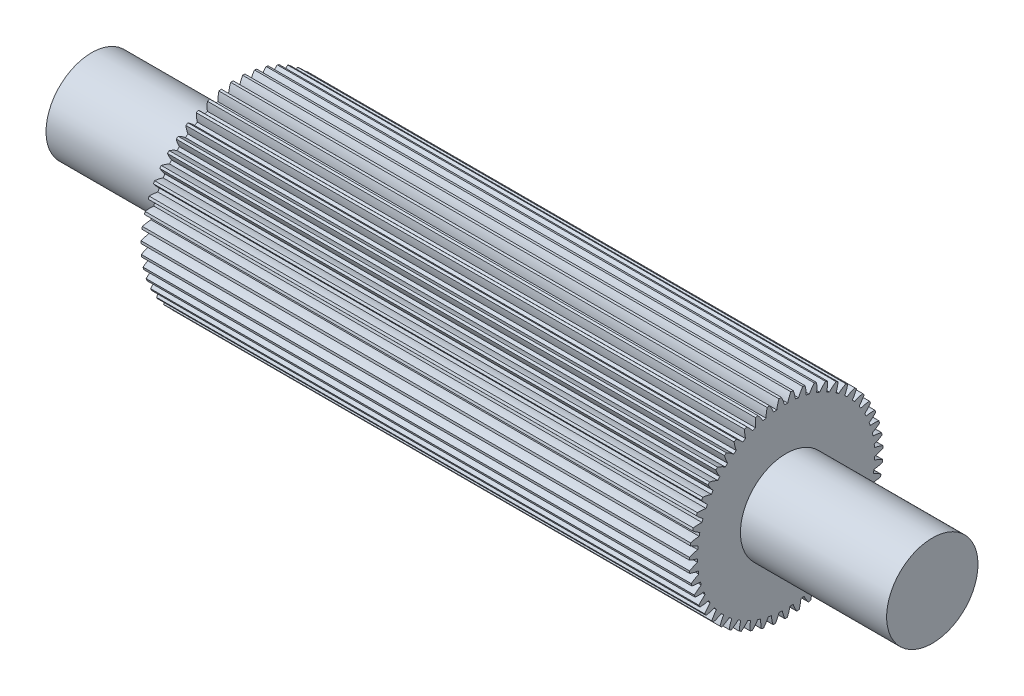
SolidWorks part; units mm, degrees
ref_plane "Plane1" through (0, 0, 0) normal (0, 0, 1) x (1, 0, 0)
ref_plane "Plane2" through (0, 0, 0) normal (0, 1, 0) x (1, 0, 0)
ref_plane "Plane3" through (0, 0, 0) normal (1, 0, 0) x (0, 0, -1)
sketch "HoldingSke" plane through (0, 0, 0) normal (0, 1, 0) x (1, 0, 0)
  line L0 (0, 0) -> (0.3147, -0.3886)
  line L1 (-15, 0) -> (100, 0) construction
  line L2 (0, 0) -> (-2.1039, 2.3779)
  line L3 (0, 0) -> (-11.863, 4.5341)
  line L4 (0, 0) -> (5.4348, 6.7114)
  line L5 (0, 0) -> (-46.8476, -17.4728)
  line L6 (0, 0) -> (-66.317, -44.7443)
  line L7 (-2.1039, 2.3779) -> (15.1161, 80.5027)
  line L8 (-76.2, 54.61) -> (-76.1, 54.61)
  line L9 (-71.009, 38.7566) -> (-53.1078, 45.2721)
  line L10 (-76.2, 71.12) -> (104.1128, 71.12)
  line L11 (0, 0) -> (-80, 0)
  line L12 (-76.2, 101.6) -> (-76.133, 101.6)
  line L13 (24.9733, 27.94) -> (52.9518, 28.4284)
  line L14 (24.9733, 27.94) -> (24.9743, 27.94)
  line L15 (24.9733, 27.94) -> (100.4006, 29.5858)
  line L16 (-63.627, -2) -> (-12.827, -2)
  circle A0 centre (0, 0) radius 0.4
  circle A1 centre (0, 0) radius 37.5
  circle A2 centre (0, 0) radius 37.5
  circle A3 centre (0, 0) radius 0.4
  dimension "Num_teeth" = 51
  dimension "Pitch_radius" = 180.3128
  dimension "Width" = 80
  dimension "Thickness" = 80
sketch "BasProSke" plane through (0, 0, 0) normal (0, 1, 0) x (1, 0, 0)
  line L0 (-10, 0) -> (60, 0) construction
  line L1 (0, 0) -> (0, 53)
  line L2 (0, 0) -> (80, 0)
  line L3 (80, 0) -> (80, 53)
  line L4 (80, 53) -> (0, 53)
  dimension "Thickness" = 80
  dimension "Diameter" = 106
revolve "Base-Revolve" add sketch "BasProSke" angle 360 about L0
sketch "TooCutSke" plane through (0, 0, 0) normal (1, 0, 0) x (0, 0, -1)
  line L1 (0, 0) -> (0, 107) construction
  line L2 (0, 0) -> (-1.6878, 50.9721) construction
  line L3 (0, 0) -> (-6.2767, 101.7652) construction
  line L4 (-1.6878, 50.9721) -> (-3.1383, 50.8826) construction
  arc A0 (0.8589, 48.4914) -> (-0.8589, 48.4914) centre (0, 0) ccw
  arc A1 (2.6252, 52.9604) -> (-2.6252, 52.9604) centre (0, 0) ccw
  circle A2 centre (0, 0) radius 51 construction
  circle A3 centre (0, 0) radius 47.9243 construction
  arc A4 (-0.8589, 48.4914) -> (-2.6252, 52.9604) centre (-20.5819, 43.2796) ccw
  arc A5 (2.6252, 52.9604) -> (0.8589, 48.4914) centre (20.5819, 43.2796) ccw
extrude "ToothCut" cut sketch "TooCutSke" along normal through all
fillet "Breaks" [suppressed] radius 0.04 tangent propagation no
fillet "RootFillets" [suppressed] radius 0.501
pattern_circular "TeethCuts" count 51 every 7.059 about axis through (-10, 0, 0) along (1, 0, 0) of "ToothCut", "RootFillets", "Breaks"
sketch "HubNeaOneSke" plane through (0, 0, 0) normal (-1, 0, 0) x (0, 0, 1)
  circle A0 centre (0, 0) radius 37.5
  dimension "Diameter" = 75
extrude "HubNearOne" [suppressed] add sketch "HubNeaOneSke" along normal blind 20.0001
sketch "HubNeaBotSke" plane through (0, 0, 0) normal (-1, 0, 0) x (0, 0, 1)
  circle A0 centre (0, 0) radius 37.5
  dimension "Diameter" = 75
extrude "HubNearBoth" [suppressed] add sketch "HubNeaBotSke" along normal blind 10
ref_plane "FarPln" through (80, 0, 0) normal (1, 0, 0) x (0, 0, -1)
sketch "HubFarSke" plane through (80, 0, 0) normal (1, 0, 0) x (0, 0, -1)
  circle A0 centre (0, 0) radius 37.5
  dimension "Diameter" = 75
extrude "HubFar" [suppressed] add sketch "HubFarSke" along normal blind 10
sketch "BorSke" plane through (0, 0, 0) normal (1, 0, 0) x (0, 0, -1)
  circle A0 centre (0, 0) radius 0.4
  dimension "Diameter" = 0.8
extrude "Bore" cut sketch "BorSke" along normal mid plane 160.0001
sketch "KeySke" plane through (0, 0, 0) normal (1, 0, 0) x (0, 0, -1)
  line L0 (-0.05, 0) -> (-0.05, 0.5)
  line L1 (-0.05, 0.5) -> (0.05, 0.5)
  line L2 (0.05, 0.5) -> (0.05, 0)
  line L3 (0, 0) -> (0, 34) construction
  line L4 (-0.05, 0) -> (0.05, 0)
extrude "Keyway" [suppressed] cut sketch "KeySke" along normal mid plane 160.0001
pattern_circular "Keyway2" [suppressed] count 2 every 90 about axis through (-10, 0, 0) along (1, 0, 0) reverse direction yes
sketch "草圖2" plane through (80, 0, 0) normal (1, 0, 0) x (0, 0, -1)
  circle A0 centre (0.4, 0) radius 25
  circle A1 centre (0, 0) radius 0.4 construction
  dimension "D1" = 50
extrude "填料-伸長1" add sketch "草圖2" along normal blind 100
extrude "填料-伸長2" add sketch "草圖2<2>" against normal blind 100 from surface starting at face at (0, 0, -0.4)
sketch "草圖2<2>" plane through (80, 0, 0) normal (1, 0, 0) x (0, 0, -1) same geometry as "草圖2"
sketch "草圖3" plane through (0, 0, 0) normal (-1, 0, 0) x (0, 0, 1)
  arc A204 (48.4948, -0.6348) -> (52.9909, 0.9804) centre (43.8929, 19.2393) ccw
  arc A205 (52.9909, 0.9804) -> (52.9508, 2.2836) centre (0, 0) ccw
  arc A206 (52.9508, 2.2836) -> (48.3638, 3.619) centre (44.9941, -16.5007) ccw
  arc A207 (48.3638, 3.619) -> (48.2053, 5.3294) centre (0, 0) ccw
  arc A208 (48.2053, 5.3294) -> (52.4688, 7.485) centre (41.196, 24.4874) ccw
  arc A209 (52.4688, 7.485) -> (52.2688, 8.7733) centre (0, 0) ccw
  arc A210 (52.2688, 8.7733) -> (47.5525, 9.5349) centre (46.6808, -10.8464) ccw
  arc A211 (47.5525, 9.5349) -> (47.185, 11.2129) centre (0, 0) ccw
  arc A212 (47.185, 11.2129) -> (51.1513, 13.876) centre (37.8745, 29.3643) ccw
  arc A213 (51.1513, 13.876) -> (50.7945, 15.13) centre (0, 0) ccw
  arc A214 (50.7945, 15.13) -> (46.0203, 15.3063) centre (47.6599, -5.0277) ccw
  arc A215 (46.0203, 15.3063) -> (45.4494, 16.9264) centre (0, 0) ccw
  arc A216 (45.4494, 16.9264) -> (49.0584, 20.0568) centre (33.9789, 33.7961) ccw
  arc A217 (49.0584, 20.0568) -> (48.5502, 21.2574) centre (0, 0) ccw
  arc A218 (48.5502, 21.2574) -> (43.7905, 20.8457) centre (47.9165, 0.8673) ccw
  arc A219 (43.7905, 20.8457) -> (43.0249, 22.3833) centre (0, 0) ccw
  arc A220 (43.0249, 22.3833) -> (46.2218, 25.9335) centre (29.5682, 37.7155) ccw
  arc A221 (46.2218, 25.9335) -> (45.5699, 27.0625) centre (0, 0) ccw
  arc A222 (45.5699, 27.0625) -> (40.8969, 26.069) centre (47.4467, 6.7491) ccw
  arc A223 (40.8969, 26.069) -> (39.9481, 27.5009) centre (0, 0) ccw
  arc A224 (39.9481, 27.5009) -> (42.6846, 31.417) centre (24.7093, 41.0633) ccw
  arc A225 (42.6846, 31.417) -> (41.8989, 32.4574) centre (0, 0) ccw
  arc A226 (41.8989, 32.4574) -> (37.3834, 30.8972) centre (46.2577, 12.5285) ccw
  arc A227 (37.3834, 30.8972) -> (36.2658, 32.2016) centre (0, 0) ccw
  arc A228 (36.2658, 32.2016) -> (38.5002, 36.4243) centre (19.4758, 43.7885) ccw
  arc A229 (38.5002, 36.4243) -> (37.5927, 37.3603) centre (0, 0) ccw
  arc A230 (37.5927, 37.3603) -> (33.3031, 35.257) centre (44.3675, 18.1181) ccw
  arc A231 (33.3031, 35.257) -> (32.0337, 36.4142) centre (0, 0) ccw
  arc A232 (32.0337, 36.4142) -> (33.7323, 40.8795) centre (13.9471, 45.85) ccw
  arc A233 (33.7323, 40.8795) -> (32.7166, 41.6968) centre (0, 0) ccw
  arc A234 (32.7166, 41.6968) -> (28.7181, 39.0823) centre (41.8047, 23.433) ccw
  arc A235 (28.7181, 39.0823) -> (27.3161, 40.0748) centre (0, 0) ccw
  arc A236 (27.3161, 40.0748) -> (28.453, 44.7149) centre (8.207, 47.2164) ccw
  arc A237 (28.453, 44.7149) -> (27.3446, 45.4013) centre (0, 0) ccw
  arc A238 (27.3446, 45.4013) -> (23.6976, 42.3152) centre (38.6082, 28.3927) ccw
  arc A239 (23.6976, 42.3152) -> (22.1843, 43.1278) centre (0, 0) ccw
  arc A240 (22.1843, 43.1278) -> (22.7424, 47.8726) centre (2.3424, 47.867) ccw
  arc A241 (22.7424, 47.8726) -> (21.558, 48.4175) centre (0, 0) ccw
  arc A242 (21.558, 48.4175) -> (18.318, 44.9066) centre (34.8264, 32.922) ccw
  arc A243 (18.318, 44.9066) -> (16.7163, 45.5271) centre (0, 0) ccw
  arc A244 (16.7163, 45.5271) -> (16.6871, 50.3045) centre (-3.5576, 47.7921) ccw
  arc A245 (16.6871, 50.3045) -> (15.4447, 50.6997) centre (0, 0) ccw
  arc A246 (15.4447, 50.6997) -> (12.6606, 46.8173) centre (30.5167, 36.9523) ccw
  arc A247 (12.6606, 46.8173) -> (10.9948, 47.2363) centre (0, 0) ccw
  arc A248 (10.9948, 47.2363) -> (10.3788, 51.9739) centre (-9.4037, 46.9927) ccw
  arc A249 (10.3788, 51.9739) -> (9.0972, 52.2134) centre (0, 0) ccw
  arc A250 (9.0972, 52.2134) -> (6.8114, 48.0183) centre (25.7444, 40.4223) ccw
  arc A251 (6.8114, 48.0183) -> (5.1067, 48.2294) centre (0, 0) ccw
  arc A252 (5.1067, 48.2294) -> (3.9131, 52.8553) centre (-15.1073, 45.4809) ccw
  arc A253 (3.9131, 52.8553) -> (2.6118, 52.9356) centre (0, 0) ccw
  arc A254 (2.6118, 52.9356) -> (0.8589, 48.4914) centre (20.5819, 43.2796) ccw
  arc A255 (0.8589, 48.4914) -> (-0.8589, 48.4914) centre (0, 0) ccw
  arc A256 (-0.8589, 48.4914) -> (-2.6118, 52.9356) centre (-20.5819, 43.2796) ccw
  arc A257 (-2.6118, 52.9356) -> (-3.9131, 52.8553) centre (0, 0) ccw
  arc A258 (-3.9131, 52.8553) -> (-5.1067, 48.2294) centre (15.1073, 45.4809) ccw
  arc A259 (-5.1067, 48.2294) -> (-6.8114, 48.0183) centre (0, 0) ccw
  arc A260 (-6.8114, 48.0183) -> (-9.0972, 52.2134) centre (-25.7444, 40.4223) ccw
  arc A261 (-9.0972, 52.2134) -> (-10.3788, 51.9739) centre (0, 0) ccw
  arc A262 (-10.3788, 51.9739) -> (-10.9948, 47.2363) centre (9.4037, 46.9927) ccw
  arc A263 (-10.9948, 47.2363) -> (-12.6606, 46.8173) centre (0, 0) ccw
  arc A264 (-12.6606, 46.8173) -> (-15.4447, 50.6997) centre (-30.5167, 36.9523) ccw
  arc A265 (-15.4447, 50.6997) -> (-16.6871, 50.3045) centre (0, 0) ccw
  arc A266 (-16.6871, 50.3045) -> (-16.7163, 45.5271) centre (3.5576, 47.7921) ccw
  arc A267 (-16.7163, 45.5271) -> (-18.318, 44.9066) centre (0, 0) ccw
  arc A268 (-18.318, 44.9066) -> (-21.558, 48.4175) centre (-34.8264, 32.922) ccw
  arc A269 (-21.558, 48.4175) -> (-22.7424, 47.8726) centre (0, 0) ccw
  arc A270 (-22.7424, 47.8726) -> (-22.1843, 43.1278) centre (-2.3424, 47.867) ccw
  arc A271 (-22.1843, 43.1278) -> (-23.6976, 42.3152) centre (0, 0) ccw
  arc A272 (-23.6976, 42.3152) -> (-27.3446, 45.4013) centre (-38.6082, 28.3927) ccw
  arc A273 (-27.3446, 45.4013) -> (-28.453, 44.7149) centre (0, 0) ccw
  arc A274 (-28.453, 44.7149) -> (-27.3161, 40.0748) centre (-8.207, 47.2164) ccw
  arc A275 (-27.3161, 40.0748) -> (-28.7181, 39.0823) centre (0, 0) ccw
  arc A276 (-28.7181, 39.0823) -> (-32.7166, 41.6968) centre (-41.8047, 23.433) ccw
  arc A277 (-32.7166, 41.6968) -> (-33.7323, 40.8795) centre (0, 0) ccw
  arc A278 (-33.7323, 40.8795) -> (-32.0337, 36.4142) centre (-13.9471, 45.85) ccw
  arc A279 (-32.0337, 36.4142) -> (-33.3031, 35.257) centre (0, 0) ccw
  arc A280 (-33.3031, 35.257) -> (-37.5927, 37.3603) centre (-44.3675, 18.1181) ccw
  arc A281 (-37.5927, 37.3603) -> (-38.5002, 36.4243) centre (0, 0) ccw
  arc A282 (-38.5002, 36.4243) -> (-36.2658, 32.2016) centre (-19.4758, 43.7885) ccw
  arc A283 (-36.2658, 32.2016) -> (-37.3834, 30.8972) centre (0, 0) ccw
  arc A284 (-37.3834, 30.8972) -> (-41.8989, 32.4574) centre (-46.2577, 12.5285) ccw
  arc A285 (-41.8989, 32.4574) -> (-42.6846, 31.417) centre (0, 0) ccw
  arc A286 (-42.6846, 31.417) -> (-39.9481, 27.5009) centre (-24.7093, 41.0633) ccw
  arc A287 (-39.9481, 27.5009) -> (-40.8969, 26.069) centre (0, 0) ccw
  arc A288 (-40.8969, 26.069) -> (-45.5699, 27.0625) centre (-47.4467, 6.7491) ccw
  arc A289 (-45.5699, 27.0625) -> (-46.2218, 25.9335) centre (0, 0) ccw
  arc A290 (-46.2218, 25.9335) -> (-43.0249, 22.3833) centre (-29.5682, 37.7155) ccw
  arc A291 (-43.0249, 22.3833) -> (-43.7905, 20.8457) centre (0, 0) ccw
  arc A292 (-43.7905, 20.8457) -> (-48.5502, 21.2574) centre (-47.9165, 0.8673) ccw
  arc A293 (-48.5502, 21.2574) -> (-49.0584, 20.0568) centre (0, 0) ccw
  arc A294 (-49.0584, 20.0568) -> (-45.4494, 16.9264) centre (-33.9789, 33.7961) ccw
  arc A295 (-45.4494, 16.9264) -> (-46.0203, 15.3063) centre (0, 0) ccw
  arc A296 (-46.0203, 15.3063) -> (-50.7945, 15.13) centre (-47.6599, -5.0277) ccw
  arc A297 (-50.7945, 15.13) -> (-51.1513, 13.876) centre (0, 0) ccw
  arc A298 (-51.1513, 13.876) -> (-47.185, 11.2129) centre (-37.8745, 29.3643) ccw
  arc A299 (-47.185, 11.2129) -> (-47.5525, 9.5349) centre (0, 0) ccw
  arc A300 (-47.5525, 9.5349) -> (-52.2688, 8.7733) centre (-46.6808, -10.8464) ccw
  arc A301 (-52.2688, 8.7733) -> (-52.4688, 7.485) centre (0, 0) ccw
  arc A302 (-52.4688, 7.485) -> (-48.2053, 5.3294) centre (-41.196, 24.4874) ccw
  arc A303 (-48.2053, 5.3294) -> (-48.3638, 3.619) centre (0, 0) ccw
  arc A304 (-48.3638, 3.619) -> (-52.9508, 2.2836) centre (-44.9941, -16.5007) ccw
  arc A305 (-52.9508, 2.2836) -> (-52.9909, 0.9804) centre (0, 0) ccw
  arc A306 (-52.9909, 0.9804) -> (-48.4948, -0.6348) centre (-43.8929, 19.2393) ccw
  arc A307 (-48.4948, -0.6348) -> (-48.4419, -2.3517) centre (0, 0) ccw
  arc A308 (-48.4419, -2.3517) -> (-52.8301, -4.2408) centre (-42.6253, -21.9049) ccw
  arc A309 (-52.8301, -4.2408) -> (-52.7098, -5.539) centre (0, 0) ccw
  arc A310 (-52.7098, -5.539) -> (-48.0493, -6.5895) centre (-45.9245, 13.6996) ccw
  arc A311 (-48.0493, -6.5895) -> (-47.7858, -8.2869) centre (0, 0) ccw
  arc A312 (-47.7858, -8.2869) -> (-51.9085, -10.7008) centre (-39.6104, -26.977) ccw
  arc A313 (-51.9085, -10.7008) -> (-51.6296, -11.9744) centre (0, 0) ccw
  arc A314 (-51.6296, -11.9744) -> (-46.8753, -12.4442) centre (-47.26, 7.9521) ccw
  arc A315 (-46.8753, -12.4442) -> (-46.4052, -14.0964) centre (0, 0) ccw
  arc A316 (-46.4052, -14.0964) -> (-50.2001, -16.9986) centre (-35.995, -31.6402) ccw
  arc A317 (-50.2001, -16.9986) -> (-49.7667, -18.2283) centre (0, 0) ccw
  arc A318 (-49.7667, -18.2283) -> (-44.9908, -18.1103) centre (-47.879, 2.0842) ccw
  arc A319 (-44.9908, -18.1103) -> (-44.3212, -19.6922) centre (0, 0) ccw
  arc A320 (-44.3212, -19.6922) -> (-47.7306, -23.0388) centre (-31.8339, -35.8238) ccw
  arc A321 (-47.7306, -23.0388) -> (-47.1495, -24.2059) centre (0, 0) ccw
  arc A322 (-47.1495, -24.2059) -> (-42.4242, -23.5019) centre (-47.7722, -3.8154) ccw
  arc A323 (-42.4242, -23.5019) -> (-41.5654, -24.9895) centre (0, 0) ccw
  arc A324 (-41.5654, -24.9895) -> (-44.5377, -28.7297) centre (-27.1903, -39.4642) ccw
  arc A325 (-44.5377, -28.7297) -> (-43.8175, -29.8165) centre (0, 0) ccw
  arc A326 (-43.8175, -29.8165) -> (-39.2145, -28.5372) centre (-46.9412, -9.6571) ccw
  arc A327 (-39.2145, -28.5372) -> (-38.1794, -29.908) centre (0, 0) ccw
  arc A328 (-38.1794, -29.908) -> (-40.6695, -33.9851) centre (-22.1345, -42.5065) ccw
  arc A329 (-40.6695, -33.9851) -> (-39.8213, -34.9752) centre (0, 0) ccw
  arc A330 (-39.8213, -34.9752) -> (-35.4104, -33.1399) centre (-45.3987, -15.3524) ccw
  arc A331 (-35.4104, -33.1399) -> (-34.2147, -34.3731) centre (0, 0) ccw
  arc A332 (-34.2147, -34.3731) -> (-36.1849, -38.7253) centre (-16.7432, -44.9044) ccw
  arc A333 (-36.1849, -38.7253) -> (-35.2214, -39.6037) centre (0, 0) ccw
  arc A334 (-35.2214, -39.6037) -> (-31.0695, -37.2403) centre (-43.168, -20.8151) ccw
  arc A335 (-31.0695, -37.2403) -> (-29.7313, -38.3171) centre (0, 0) ccw
  arc A336 (-29.7313, -38.3171) -> (-31.1518, -42.8785) centre (-11.0981, -46.6216) ccw
  arc A337 (-31.1518, -42.8785) -> (-30.0876, -43.6318) centre (0, 0) ccw
  arc A338 (-30.0876, -43.6318) -> (-26.2576, -40.7761) centre (-40.2829, -25.9621) ccw
  arc A339 (-26.2576, -40.7761) -> (-24.7972, -41.6803) centre (0, 0) ccw
  arc A340 (-24.7972, -41.6803) -> (-25.6464, -46.3817) centre (-5.2847, -47.6321) ccw
  arc A341 (-25.6464, -46.3817) -> (-24.4977, -46.9985) centre (0, 0) ccw
  arc A342 (-24.4977, -46.9985) -> (-21.0477, -43.6938) centre (-36.7871, -30.7156) ccw
  arc A343 (-21.0477, -43.6938) -> (-19.4872, -44.4117) centre (0, 0) ccw
  arc A344 (-19.4872, -44.4117) -> (-19.7522, -49.1818) centre (0.6087, -47.9205) ccw
  arc A345 (-19.7522, -49.1818) -> (-18.5365, -49.6528) centre (0, 0) ccw
  arc A346 (-18.5365, -49.6528) -> (-15.5187, -45.9491) centre (-32.7337, -35.0035) ccw
  arc A347 (-15.5187, -45.9491) -> (-13.8819, -46.4699) centre (0, 0) ccw
  arc A348 (-13.8819, -46.4699) -> (-13.5586, -51.2363) centre (6.493, -47.4824) ccw
  arc A349 (-13.5586, -51.2363) -> (-12.2943, -51.5544) centre (0, 0) ccw
  arc A350 (-12.2943, -51.5544) -> (-9.7545, -47.5079) centre (-28.184, -38.7608) ccw
  arc A351 (-9.7545, -47.5079) -> (-8.066, -47.8236) centre (0, 0) ccw
  arc A352 (-8.066, -47.8236) -> (-7.1595, -52.5142) centre (12.2788, -46.3246) ccw
  arc A353 (-7.1595, -52.5142) -> (-5.8656, -52.6744) centre (0, 0) ccw
  arc A354 (-5.8656, -52.6744) -> (-3.8424, -48.3466) centre (-23.2072, -41.9305) ccw
  arc A355 (-3.8424, -48.3466) -> (-2.1279, -48.4523) centre (0, 0) ccw
  arc A356 (-2.1279, -48.4523) -> (-0.6519, -52.996) centre (17.8785, -44.4646) ccw
  arc A357 (-0.6519, -52.996) -> (0.6519, -52.996) centre (0, 0) ccw
  arc A358 (0.6519, -52.996) -> (2.1279, -48.4523) centre (-17.8785, -44.4646) ccw
  arc A359 (2.1279, -48.4523) -> (3.8424, -48.3466) centre (0, 0) ccw
  arc A360 (3.8424, -48.3466) -> (5.8656, -52.6744) centre (23.2072, -41.9305) ccw
  arc A361 (5.8656, -52.6744) -> (7.1595, -52.5142) centre (0, 0) ccw
  arc A362 (7.1595, -52.5142) -> (8.066, -47.8236) centre (-12.2788, -46.3246) ccw
  arc A363 (8.066, -47.8236) -> (9.7545, -47.5079) centre (0, 0) ccw
  arc A364 (9.7545, -47.5079) -> (12.2943, -51.5544) centre (28.184, -38.7608) ccw
  arc A365 (12.2943, -51.5544) -> (13.5586, -51.2363) centre (0, 0) ccw
  arc A366 (13.5586, -51.2363) -> (13.8819, -46.4699) centre (-6.493, -47.4824) ccw
  arc A367 (13.8819, -46.4699) -> (15.5187, -45.9491) centre (0, 0) ccw
  arc A368 (15.5187, -45.9491) -> (18.5365, -49.6528) centre (32.7337, -35.0035) ccw
  arc A369 (18.5365, -49.6528) -> (19.7522, -49.1818) centre (0, 0) ccw
  arc A370 (19.7522, -49.1818) -> (19.4872, -44.4117) centre (-0.6087, -47.9205) ccw
  arc A371 (19.4872, -44.4117) -> (21.0477, -43.6938) centre (0, 0) ccw
  arc A372 (21.0477, -43.6938) -> (24.4977, -46.9985) centre (36.7871, -30.7156) ccw
  arc A373 (24.4977, -46.9985) -> (25.6464, -46.3817) centre (0, 0) ccw
  arc A374 (25.6464, -46.3817) -> (24.7972, -41.6803) centre (5.2847, -47.6321) ccw
  arc A375 (24.7972, -41.6803) -> (26.2576, -40.7761) centre (0, 0) ccw
  arc A376 (26.2576, -40.7761) -> (30.0876, -43.6318) centre (40.2829, -25.9621) ccw
  arc A377 (30.0876, -43.6318) -> (31.1518, -42.8785) centre (0, 0) ccw
  arc A378 (31.1518, -42.8785) -> (29.7313, -38.3171) centre (11.0981, -46.6216) ccw
  arc A379 (29.7313, -38.3171) -> (31.0695, -37.2403) centre (0, 0) ccw
  arc A380 (31.0695, -37.2403) -> (35.2214, -39.6037) centre (43.168, -20.8151) ccw
  arc A381 (35.2214, -39.6037) -> (36.1849, -38.7253) centre (0, 0) ccw
  arc A382 (36.1849, -38.7253) -> (34.2147, -34.3731) centre (16.7432, -44.9044) ccw
  arc A383 (34.2147, -34.3731) -> (35.4104, -33.1399) centre (0, 0) ccw
  arc A384 (35.4104, -33.1399) -> (39.8213, -34.9752) centre (45.3987, -15.3524) ccw
  arc A385 (39.8213, -34.9752) -> (40.6695, -33.9851) centre (0, 0) ccw
  arc A386 (40.6695, -33.9851) -> (38.1794, -29.908) centre (22.1345, -42.5065) ccw
  arc A387 (38.1794, -29.908) -> (39.2145, -28.5372) centre (0, 0) ccw
  arc A388 (39.2145, -28.5372) -> (43.8175, -29.8165) centre (46.9412, -9.6571) ccw
  arc A389 (43.8175, -29.8165) -> (44.5377, -28.7297) centre (0, 0) ccw
  arc A390 (44.5377, -28.7297) -> (41.5654, -24.9895) centre (27.1903, -39.4642) ccw
  arc A391 (41.5654, -24.9895) -> (42.4242, -23.5019) centre (0, 0) ccw
  arc A392 (42.4242, -23.5019) -> (47.1495, -24.2059) centre (47.7722, -3.8154) ccw
  arc A393 (47.1495, -24.2059) -> (47.7306, -23.0388) centre (0, 0) ccw
  arc A394 (47.7306, -23.0388) -> (44.3212, -19.6922) centre (31.8339, -35.8238) ccw
  arc A395 (44.3212, -19.6922) -> (44.9908, -18.1103) centre (0, 0) ccw
  arc A396 (44.9908, -18.1103) -> (49.7667, -18.2283) centre (47.879, 2.0842) ccw
  arc A397 (49.7667, -18.2283) -> (50.2001, -16.9986) centre (0, 0) ccw
  arc A398 (50.2001, -16.9986) -> (46.4052, -14.0964) centre (35.995, -31.6402) ccw
  arc A399 (46.4052, -14.0964) -> (46.8753, -12.4442) centre (0, 0) ccw
  arc A400 (46.8753, -12.4442) -> (51.6296, -11.9744) centre (47.26, 7.9521) ccw
  arc A401 (51.6296, -11.9744) -> (51.9085, -10.7008) centre (0, 0) ccw
  arc A402 (51.9085, -10.7008) -> (47.7858, -8.2869) centre (39.6104, -26.977) ccw
  arc A403 (47.7858, -8.2869) -> (48.0493, -6.5895) centre (0, 0) ccw
  arc A404 (48.0493, -6.5895) -> (52.7098, -5.539) centre (45.9245, 13.6996) ccw
  arc A405 (52.7098, -5.539) -> (52.8301, -4.2408) centre (0, 0) ccw
  arc A406 (52.8301, -4.2408) -> (48.4419, -2.3517) centre (42.6253, -21.9049) ccw
  arc A407 (48.4419, -2.3517) -> (48.4948, -0.6348) centre (0, 0) ccw
  arc A408 (48.4948, -0.6348) -> (52.9909, 0.9804) centre (43.8929, 19.2393) ccw
  arc A409 (52.9909, 0.9804) -> (52.9508, 2.2836) centre (0, 0) ccw
  arc A410 (52.9508, 2.2836) -> (48.3638, 3.619) centre (44.9941, -16.5007) ccw
  arc A411 (48.3638, 3.619) -> (48.2053, 5.3294) centre (0, 0) ccw
  arc A412 (48.2053, 5.3294) -> (52.4688, 7.485) centre (41.196, 24.4874) ccw
  arc A413 (52.4688, 7.485) -> (52.2688, 8.7733) centre (0, 0) ccw
  arc A414 (52.2688, 8.7733) -> (47.5525, 9.5349) centre (46.6808, -10.8464) ccw
  arc A415 (47.5525, 9.5349) -> (47.185, 11.2129) centre (0, 0) ccw
  arc A416 (47.185, 11.2129) -> (51.1513, 13.876) centre (37.8745, 29.3643) ccw
  arc A417 (51.1513, 13.876) -> (50.7945, 15.13) centre (0, 0) ccw
  arc A418 (50.7945, 15.13) -> (46.0203, 15.3063) centre (47.6599, -5.0277) ccw
  arc A419 (46.0203, 15.3063) -> (45.4494, 16.9264) centre (0, 0) ccw
  arc A420 (45.4494, 16.9264) -> (49.0584, 20.0568) centre (33.9789, 33.7961) ccw
  arc A421 (49.0584, 20.0568) -> (48.5502, 21.2574) centre (0, 0) ccw
  arc A422 (48.5502, 21.2574) -> (43.7905, 20.8457) centre (47.9165, 0.8673) ccw
  arc A423 (43.7905, 20.8457) -> (43.0249, 22.3833) centre (0, 0) ccw
  arc A424 (43.0249, 22.3833) -> (46.2218, 25.9335) centre (29.5682, 37.7155) ccw
  arc A425 (46.2218, 25.9335) -> (45.5699, 27.0625) centre (0, 0) ccw
  arc A426 (45.5699, 27.0625) -> (40.8969, 26.069) centre (47.4467, 6.7491) ccw
  arc A427 (40.8969, 26.069) -> (39.9481, 27.5009) centre (0, 0) ccw
  arc A428 (39.9481, 27.5009) -> (42.6846, 31.417) centre (24.7093, 41.0633) ccw
  arc A429 (42.6846, 31.417) -> (41.8989, 32.4574) centre (0, 0) ccw
  arc A430 (41.8989, 32.4574) -> (37.3834, 30.8972) centre (46.2577, 12.5285) ccw
  arc A431 (37.3834, 30.8972) -> (36.2658, 32.2016) centre (0, 0) ccw
  arc A432 (36.2658, 32.2016) -> (38.5002, 36.4243) centre (19.4758, 43.7885) ccw
  arc A433 (38.5002, 36.4243) -> (37.5927, 37.3603) centre (0, 0) ccw
  arc A434 (37.5927, 37.3603) -> (33.3031, 35.257) centre (44.3675, 18.1181) ccw
  arc A435 (33.3031, 35.257) -> (32.0337, 36.4142) centre (0, 0) ccw
  arc A436 (32.0337, 36.4142) -> (33.7323, 40.8795) centre (13.9471, 45.85) ccw
  arc A437 (33.7323, 40.8795) -> (32.7166, 41.6968) centre (0, 0) ccw
  arc A438 (32.7166, 41.6968) -> (28.7181, 39.0823) centre (41.8047, 23.433) ccw
  arc A439 (28.7181, 39.0823) -> (27.3161, 40.0748) centre (0, 0) ccw
  arc A440 (27.3161, 40.0748) -> (28.453, 44.7149) centre (8.207, 47.2164) ccw
  arc A441 (28.453, 44.7149) -> (27.3446, 45.4013) centre (0, 0) ccw
  arc A442 (27.3446, 45.4013) -> (23.6976, 42.3152) centre (38.6082, 28.3927) ccw
  arc A443 (23.6976, 42.3152) -> (22.1843, 43.1278) centre (0, 0) ccw
  arc A444 (22.1843, 43.1278) -> (22.7424, 47.8726) centre (2.3424, 47.867) ccw
  arc A445 (22.7424, 47.8726) -> (21.558, 48.4175) centre (0, 0) ccw
  arc A446 (21.558, 48.4175) -> (18.318, 44.9066) centre (34.8264, 32.922) ccw
  arc A447 (18.318, 44.9066) -> (16.7163, 45.5271) centre (0, 0) ccw
  arc A448 (16.7163, 45.5271) -> (16.6871, 50.3045) centre (-3.5576, 47.7921) ccw
  arc A449 (16.6871, 50.3045) -> (15.4447, 50.6997) centre (0, 0) ccw
  arc A450 (15.4447, 50.6997) -> (12.6606, 46.8173) centre (30.5167, 36.9523) ccw
  arc A451 (12.6606, 46.8173) -> (10.9948, 47.2363) centre (0, 0) ccw
  arc A452 (10.9948, 47.2363) -> (10.3788, 51.9739) centre (-9.4037, 46.9927) ccw
  arc A453 (10.3788, 51.9739) -> (9.0972, 52.2134) centre (0, 0) ccw
  arc A454 (9.0972, 52.2134) -> (6.8114, 48.0183) centre (25.7444, 40.4223) ccw
  arc A455 (6.8114, 48.0183) -> (5.1067, 48.2294) centre (0, 0) ccw
  arc A456 (5.1067, 48.2294) -> (3.9131, 52.8553) centre (-15.1073, 45.4809) ccw
  arc A457 (3.9131, 52.8553) -> (2.6118, 52.9356) centre (0, 0) ccw
  arc A458 (2.6118, 52.9356) -> (0.8589, 48.4914) centre (20.5819, 43.2796) ccw
  arc A459 (0.8589, 48.4914) -> (-0.8589, 48.4914) centre (0, 0) ccw
  arc A460 (-0.8589, 48.4914) -> (-2.6118, 52.9356) centre (-20.5819, 43.2796) ccw
  arc A461 (-2.6118, 52.9356) -> (-3.9131, 52.8553) centre (0, 0) ccw
  arc A462 (-3.9131, 52.8553) -> (-5.1067, 48.2294) centre (15.1073, 45.4809) ccw
  arc A463 (-5.1067, 48.2294) -> (-6.8114, 48.0183) centre (0, 0) ccw
  arc A464 (-6.8114, 48.0183) -> (-9.0972, 52.2134) centre (-25.7444, 40.4223) ccw
  arc A465 (-9.0972, 52.2134) -> (-10.3788, 51.9739) centre (0, 0) ccw
  arc A466 (-10.3788, 51.9739) -> (-10.9948, 47.2363) centre (9.4037, 46.9927) ccw
  arc A467 (-10.9948, 47.2363) -> (-12.6606, 46.8173) centre (0, 0) ccw
  arc A468 (-12.6606, 46.8173) -> (-15.4447, 50.6997) centre (-30.5167, 36.9523) ccw
  arc A469 (-15.4447, 50.6997) -> (-16.6871, 50.3045) centre (0, 0) ccw
  arc A470 (-16.6871, 50.3045) -> (-16.7163, 45.5271) centre (3.5576, 47.7921) ccw
  arc A471 (-16.7163, 45.5271) -> (-18.318, 44.9066) centre (0, 0) ccw
  arc A472 (-18.318, 44.9066) -> (-21.558, 48.4175) centre (-34.8264, 32.922) ccw
  arc A473 (-21.558, 48.4175) -> (-22.7424, 47.8726) centre (0, 0) ccw
  arc A474 (-22.7424, 47.8726) -> (-22.1843, 43.1278) centre (-2.3424, 47.867) ccw
  arc A475 (-22.1843, 43.1278) -> (-23.6976, 42.3152) centre (0, 0) ccw
  arc A476 (-23.6976, 42.3152) -> (-27.3446, 45.4013) centre (-38.6082, 28.3927) ccw
  arc A477 (-27.3446, 45.4013) -> (-28.453, 44.7149) centre (0, 0) ccw
  arc A478 (-28.453, 44.7149) -> (-27.3161, 40.0748) centre (-8.207, 47.2164) ccw
  arc A479 (-27.3161, 40.0748) -> (-28.7181, 39.0823) centre (0, 0) ccw
  arc A480 (-28.7181, 39.0823) -> (-32.7166, 41.6968) centre (-41.8047, 23.433) ccw
  arc A481 (-32.7166, 41.6968) -> (-33.7323, 40.8795) centre (0, 0) ccw
  arc A482 (-33.7323, 40.8795) -> (-32.0337, 36.4142) centre (-13.9471, 45.85) ccw
  arc A483 (-32.0337, 36.4142) -> (-33.3031, 35.257) centre (0, 0) ccw
  arc A484 (-33.3031, 35.257) -> (-37.5927, 37.3603) centre (-44.3675, 18.1181) ccw
  arc A485 (-37.5927, 37.3603) -> (-38.5002, 36.4243) centre (0, 0) ccw
  arc A486 (-38.5002, 36.4243) -> (-36.2658, 32.2016) centre (-19.4758, 43.7885) ccw
  arc A487 (-36.2658, 32.2016) -> (-37.3834, 30.8972) centre (0, 0) ccw
  arc A488 (-37.3834, 30.8972) -> (-41.8989, 32.4574) centre (-46.2577, 12.5285) ccw
  arc A489 (-41.8989, 32.4574) -> (-42.6846, 31.417) centre (0, 0) ccw
  arc A490 (-42.6846, 31.417) -> (-39.9481, 27.5009) centre (-24.7093, 41.0633) ccw
  arc A491 (-39.9481, 27.5009) -> (-40.8969, 26.069) centre (0, 0) ccw
  arc A492 (-40.8969, 26.069) -> (-45.5699, 27.0625) centre (-47.4467, 6.7491) ccw
  arc A493 (-45.5699, 27.0625) -> (-46.2218, 25.9335) centre (0, 0) ccw
  arc A494 (-46.2218, 25.9335) -> (-43.0249, 22.3833) centre (-29.5682, 37.7155) ccw
  arc A495 (-43.0249, 22.3833) -> (-43.7905, 20.8457) centre (0, 0) ccw
  arc A496 (-43.7905, 20.8457) -> (-48.5502, 21.2574) centre (-47.9165, 0.8673) ccw
  arc A497 (-48.5502, 21.2574) -> (-49.0584, 20.0568) centre (0, 0) ccw
  arc A498 (-49.0584, 20.0568) -> (-45.4494, 16.9264) centre (-33.9789, 33.7961) ccw
  arc A499 (-45.4494, 16.9264) -> (-46.0203, 15.3063) centre (0, 0) ccw
  arc A500 (-46.0203, 15.3063) -> (-50.7945, 15.13) centre (-47.6599, -5.0277) ccw
  arc A501 (-50.7945, 15.13) -> (-51.1513, 13.876) centre (0, 0) ccw
  arc A502 (-51.1513, 13.876) -> (-47.185, 11.2129) centre (-37.8745, 29.3643) ccw
  arc A503 (-47.185, 11.2129) -> (-47.5525, 9.5349) centre (0, 0) ccw
  arc A504 (-47.5525, 9.5349) -> (-52.2688, 8.7733) centre (-46.6808, -10.8464) ccw
  arc A505 (-52.2688, 8.7733) -> (-52.4688, 7.485) centre (0, 0) ccw
  arc A506 (-52.4688, 7.485) -> (-48.2053, 5.3294) centre (-41.196, 24.4874) ccw
  arc A507 (-48.2053, 5.3294) -> (-48.3638, 3.619) centre (0, 0) ccw
  arc A508 (-48.3638, 3.619) -> (-52.9508, 2.2836) centre (-44.9941, -16.5007) ccw
  arc A509 (-52.9508, 2.2836) -> (-52.9909, 0.9804) centre (0, 0) ccw
  arc A510 (-52.9909, 0.9804) -> (-48.4948, -0.6348) centre (-43.8929, 19.2393) ccw
  arc A511 (-48.4948, -0.6348) -> (-48.4419, -2.3517) centre (0, 0) ccw
  arc A512 (-48.4419, -2.3517) -> (-52.8301, -4.2408) centre (-42.6253, -21.9049) ccw
  arc A513 (-52.8301, -4.2408) -> (-52.7098, -5.539) centre (0, 0) ccw
  arc A514 (-52.7098, -5.539) -> (-48.0493, -6.5895) centre (-45.9245, 13.6996) ccw
  arc A515 (-48.0493, -6.5895) -> (-47.7858, -8.2869) centre (0, 0) ccw
  arc A516 (-47.7858, -8.2869) -> (-51.9085, -10.7008) centre (-39.6104, -26.977) ccw
  arc A517 (-51.9085, -10.7008) -> (-51.6296, -11.9744) centre (0, 0) ccw
  arc A518 (-51.6296, -11.9744) -> (-46.8753, -12.4442) centre (-47.26, 7.9521) ccw
  arc A519 (-46.8753, -12.4442) -> (-46.4052, -14.0964) centre (0, 0) ccw
  arc A520 (-46.4052, -14.0964) -> (-50.2001, -16.9986) centre (-35.995, -31.6402) ccw
  arc A521 (-50.2001, -16.9986) -> (-49.7667, -18.2283) centre (0, 0) ccw
  arc A522 (-49.7667, -18.2283) -> (-44.9908, -18.1103) centre (-47.879, 2.0842) ccw
  arc A523 (-44.9908, -18.1103) -> (-44.3212, -19.6922) centre (0, 0) ccw
  arc A524 (-44.3212, -19.6922) -> (-47.7306, -23.0388) centre (-31.8339, -35.8238) ccw
  arc A525 (-47.7306, -23.0388) -> (-47.1495, -24.2059) centre (0, 0) ccw
  arc A526 (-47.1495, -24.2059) -> (-42.4242, -23.5019) centre (-47.7722, -3.8154) ccw
  arc A527 (-42.4242, -23.5019) -> (-41.5654, -24.9895) centre (0, 0) ccw
  arc A528 (-41.5654, -24.9895) -> (-44.5377, -28.7297) centre (-27.1903, -39.4642) ccw
  arc A529 (-44.5377, -28.7297) -> (-43.8175, -29.8165) centre (0, 0) ccw
  arc A530 (-43.8175, -29.8165) -> (-39.2145, -28.5372) centre (-46.9412, -9.6571) ccw
  arc A531 (-39.2145, -28.5372) -> (-38.1794, -29.908) centre (0, 0) ccw
  arc A532 (-38.1794, -29.908) -> (-40.6695, -33.9851) centre (-22.1345, -42.5065) ccw
  arc A533 (-40.6695, -33.9851) -> (-39.8213, -34.9752) centre (0, 0) ccw
  arc A534 (-39.8213, -34.9752) -> (-35.4104, -33.1399) centre (-45.3987, -15.3524) ccw
  arc A535 (-35.4104, -33.1399) -> (-34.2147, -34.3731) centre (0, 0) ccw
  arc A536 (-34.2147, -34.3731) -> (-36.1849, -38.7253) centre (-16.7432, -44.9044) ccw
  arc A537 (-36.1849, -38.7253) -> (-35.2214, -39.6037) centre (0, 0) ccw
  arc A538 (-35.2214, -39.6037) -> (-31.0695, -37.2403) centre (-43.168, -20.8151) ccw
  arc A539 (-31.0695, -37.2403) -> (-29.7313, -38.3171) centre (0, 0) ccw
  arc A540 (-29.7313, -38.3171) -> (-31.1518, -42.8785) centre (-11.0981, -46.6216) ccw
  arc A541 (-31.1518, -42.8785) -> (-30.0876, -43.6318) centre (0, 0) ccw
  arc A542 (-30.0876, -43.6318) -> (-26.2576, -40.7761) centre (-40.2829, -25.9621) ccw
  arc A543 (-26.2576, -40.7761) -> (-24.7972, -41.6803) centre (0, 0) ccw
  arc A544 (-24.7972, -41.6803) -> (-25.6464, -46.3817) centre (-5.2847, -47.6321) ccw
  arc A545 (-25.6464, -46.3817) -> (-24.4977, -46.9985) centre (0, 0) ccw
  arc A546 (-24.4977, -46.9985) -> (-21.0477, -43.6938) centre (-36.7871, -30.7156) ccw
  arc A547 (-21.0477, -43.6938) -> (-19.4872, -44.4117) centre (0, 0) ccw
  arc A548 (-19.4872, -44.4117) -> (-19.7522, -49.1818) centre (0.6087, -47.9205) ccw
  arc A549 (-19.7522, -49.1818) -> (-18.5365, -49.6528) centre (0, 0) ccw
  arc A550 (-18.5365, -49.6528) -> (-15.5187, -45.9491) centre (-32.7337, -35.0035) ccw
  arc A551 (-15.5187, -45.9491) -> (-13.8819, -46.4699) centre (0, 0) ccw
  arc A552 (-13.8819, -46.4699) -> (-13.5586, -51.2363) centre (6.493, -47.4824) ccw
  arc A553 (-13.5586, -51.2363) -> (-12.2943, -51.5544) centre (0, 0) ccw
  arc A554 (-12.2943, -51.5544) -> (-9.7545, -47.5079) centre (-28.184, -38.7608) ccw
  arc A555 (-9.7545, -47.5079) -> (-8.066, -47.8236) centre (0, 0) ccw
  arc A556 (-8.066, -47.8236) -> (-7.1595, -52.5142) centre (12.2788, -46.3246) ccw
  arc A557 (-7.1595, -52.5142) -> (-5.8656, -52.6744) centre (0, 0) ccw
  arc A558 (-5.8656, -52.6744) -> (-3.8424, -48.3466) centre (-23.2072, -41.9305) ccw
  arc A559 (-3.8424, -48.3466) -> (-2.1279, -48.4523) centre (0, 0) ccw
  arc A560 (-2.1279, -48.4523) -> (-0.6519, -52.996) centre (17.8785, -44.4646) ccw
  arc A561 (-0.6519, -52.996) -> (0.6519, -52.996) centre (0, 0) ccw
  arc A562 (0.6519, -52.996) -> (2.1279, -48.4523) centre (-17.8785, -44.4646) ccw
  arc A563 (2.1279, -48.4523) -> (3.8424, -48.3466) centre (0, 0) ccw
  arc A564 (3.8424, -48.3466) -> (5.8656, -52.6744) centre (23.2072, -41.9305) ccw
  arc A565 (5.8656, -52.6744) -> (7.1595, -52.5142) centre (0, 0) ccw
  arc A566 (7.1595, -52.5142) -> (8.066, -47.8236) centre (-12.2788, -46.3246) ccw
  arc A567 (8.066, -47.8236) -> (9.7545, -47.5079) centre (0, 0) ccw
  arc A568 (9.7545, -47.5079) -> (12.2943, -51.5544) centre (28.184, -38.7608) ccw
  arc A569 (12.2943, -51.5544) -> (13.5586, -51.2363) centre (0, 0) ccw
  arc A570 (13.5586, -51.2363) -> (13.8819, -46.4699) centre (-6.493, -47.4824) ccw
  arc A571 (13.8819, -46.4699) -> (15.5187, -45.9491) centre (0, 0) ccw
  arc A572 (15.5187, -45.9491) -> (18.5365, -49.6528) centre (32.7337, -35.0035) ccw
  arc A573 (18.5365, -49.6528) -> (19.7522, -49.1818) centre (0, 0) ccw
  arc A574 (19.7522, -49.1818) -> (19.4872, -44.4117) centre (-0.6087, -47.9205) ccw
  arc A575 (19.4872, -44.4117) -> (21.0477, -43.6938) centre (0, 0) ccw
  arc A576 (21.0477, -43.6938) -> (24.4977, -46.9985) centre (36.7871, -30.7156) ccw
  arc A577 (24.4977, -46.9985) -> (25.6464, -46.3817) centre (0, 0) ccw
  arc A578 (25.6464, -46.3817) -> (24.7972, -41.6803) centre (5.2847, -47.6321) ccw
  arc A579 (24.7972, -41.6803) -> (26.2576, -40.7761) centre (0, 0) ccw
  arc A580 (26.2576, -40.7761) -> (30.0876, -43.6318) centre (40.2829, -25.9621) ccw
  arc A581 (30.0876, -43.6318) -> (31.1518, -42.8785) centre (0, 0) ccw
  arc A582 (31.1518, -42.8785) -> (29.7313, -38.3171) centre (11.0981, -46.6216) ccw
  arc A583 (29.7313, -38.3171) -> (31.0695, -37.2403) centre (0, 0) ccw
  arc A584 (31.0695, -37.2403) -> (35.2214, -39.6037) centre (43.168, -20.8151) ccw
  arc A585 (35.2214, -39.6037) -> (36.1849, -38.7253) centre (0, 0) ccw
  arc A586 (36.1849, -38.7253) -> (34.2147, -34.3731) centre (16.7432, -44.9044) ccw
  arc A587 (34.2147, -34.3731) -> (35.4104, -33.1399) centre (0, 0) ccw
  arc A588 (35.4104, -33.1399) -> (39.8213, -34.9752) centre (45.3987, -15.3524) ccw
  arc A589 (39.8213, -34.9752) -> (40.6695, -33.9851) centre (0, 0) ccw
  arc A590 (40.6695, -33.9851) -> (38.1794, -29.908) centre (22.1345, -42.5065) ccw
  arc A591 (38.1794, -29.908) -> (39.2145, -28.5372) centre (0, 0) ccw
  arc A592 (39.2145, -28.5372) -> (43.8175, -29.8165) centre (46.9412, -9.6571) ccw
  arc A593 (43.8175, -29.8165) -> (44.5377, -28.7297) centre (0, 0) ccw
  arc A594 (44.5377, -28.7297) -> (41.5654, -24.9895) centre (27.1903, -39.4642) ccw
  arc A595 (41.5654, -24.9895) -> (42.4242, -23.5019) centre (0, 0) ccw
  arc A596 (42.4242, -23.5019) -> (47.1495, -24.2059) centre (47.7722, -3.8154) ccw
  arc A597 (47.1495, -24.2059) -> (47.7306, -23.0388) centre (0, 0) ccw
  arc A598 (47.7306, -23.0388) -> (44.3212, -19.6922) centre (31.8339, -35.8238) ccw
  arc A599 (44.3212, -19.6922) -> (44.9908, -18.1103) centre (0, 0) ccw
  arc A600 (44.9908, -18.1103) -> (49.7667, -18.2283) centre (47.879, 2.0842) ccw
  arc A601 (49.7667, -18.2283) -> (50.2001, -16.9986) centre (0, 0) ccw
  arc A602 (50.2001, -16.9986) -> (46.4052, -14.0964) centre (35.995, -31.6402) ccw
  arc A603 (46.4052, -14.0964) -> (46.8753, -12.4442) centre (0, 0) ccw
  arc A604 (46.8753, -12.4442) -> (51.6296, -11.9744) centre (47.26, 7.9521) ccw
  arc A605 (51.6296, -11.9744) -> (51.9085, -10.7008) centre (0, 0) ccw
  arc A606 (51.9085, -10.7008) -> (47.7858, -8.2869) centre (39.6104, -26.977) ccw
  arc A607 (47.7858, -8.2869) -> (48.0493, -6.5895) centre (0, 0) ccw
  arc A608 (48.0493, -6.5895) -> (52.7098, -5.539) centre (45.9245, 13.6996) ccw
  arc A609 (52.7098, -5.539) -> (52.8301, -4.2408) centre (0, 0) ccw
  arc A610 (52.8301, -4.2408) -> (48.4419, -2.3517) centre (42.6253, -21.9049) ccw
  arc A611 (48.4419, -2.3517) -> (48.4948, -0.6348) centre (0, 0) ccw
  dimension "D1" = 0
extrude "填料-伸長3" add sketch "草圖3" along normal blind 110
sketch "草圖4" plane through (80, 0, 0) normal (1, 0, 0) x (0, 0, -1)
  arc A204 (-52.9909, 0.9804) -> (-48.4948, -0.6348) centre (-43.8929, 19.2393) ccw
  arc A205 (-48.4948, -0.6348) -> (-48.4419, -2.3517) centre (0, 0) ccw
  arc A206 (-48.4419, -2.3517) -> (-52.8301, -4.2408) centre (-42.6253, -21.9049) ccw
  arc A207 (-52.8301, -4.2408) -> (-52.7098, -5.539) centre (0, 0) ccw
  arc A208 (-52.7098, -5.539) -> (-48.0493, -6.5895) centre (-45.9245, 13.6996) ccw
  arc A209 (-48.0493, -6.5895) -> (-47.7858, -8.2869) centre (0, 0) ccw
  arc A210 (-47.7858, -8.2869) -> (-51.9085, -10.7008) centre (-39.6104, -26.977) ccw
  arc A211 (-51.9085, -10.7008) -> (-51.6296, -11.9744) centre (0, 0) ccw
  arc A212 (-51.6296, -11.9744) -> (-46.8753, -12.4442) centre (-47.26, 7.9521) ccw
  arc A213 (-46.8753, -12.4442) -> (-46.4052, -14.0964) centre (0, 0) ccw
  arc A214 (-46.4052, -14.0964) -> (-50.2001, -16.9986) centre (-35.995, -31.6402) ccw
  arc A215 (-50.2001, -16.9986) -> (-49.7667, -18.2283) centre (0, 0) ccw
  arc A216 (-49.7667, -18.2283) -> (-44.9908, -18.1103) centre (-47.879, 2.0842) ccw
  arc A217 (-44.9908, -18.1103) -> (-44.3212, -19.6922) centre (0, 0) ccw
  arc A218 (-44.3212, -19.6922) -> (-47.7306, -23.0388) centre (-31.8339, -35.8238) ccw
  arc A219 (-47.7306, -23.0388) -> (-47.1495, -24.2059) centre (0, 0) ccw
  arc A220 (-47.1495, -24.2059) -> (-42.4242, -23.5019) centre (-47.7722, -3.8154) ccw
  arc A221 (-42.4242, -23.5019) -> (-41.5654, -24.9895) centre (0, 0) ccw
  arc A222 (-41.5654, -24.9895) -> (-44.5377, -28.7297) centre (-27.1903, -39.4642) ccw
  arc A223 (-44.5377, -28.7297) -> (-43.8175, -29.8165) centre (0, 0) ccw
  arc A224 (-43.8175, -29.8165) -> (-39.2145, -28.5372) centre (-46.9412, -9.6571) ccw
  arc A225 (-39.2145, -28.5372) -> (-38.1794, -29.908) centre (0, 0) ccw
  arc A226 (-38.1794, -29.908) -> (-40.6695, -33.9851) centre (-22.1345, -42.5065) ccw
  arc A227 (-40.6695, -33.9851) -> (-39.8213, -34.9752) centre (0, 0) ccw
  arc A228 (-39.8213, -34.9752) -> (-35.4104, -33.1399) centre (-45.3987, -15.3524) ccw
  arc A229 (-35.4104, -33.1399) -> (-34.2147, -34.3731) centre (0, 0) ccw
  arc A230 (-34.2147, -34.3731) -> (-36.1849, -38.7253) centre (-16.7432, -44.9044) ccw
  arc A231 (-36.1849, -38.7253) -> (-35.2214, -39.6037) centre (0, 0) ccw
  arc A232 (-35.2214, -39.6037) -> (-31.0695, -37.2403) centre (-43.168, -20.8151) ccw
  arc A233 (-31.0695, -37.2403) -> (-29.7313, -38.3171) centre (0, 0) ccw
  arc A234 (-29.7313, -38.3171) -> (-31.1518, -42.8785) centre (-11.0981, -46.6216) ccw
  arc A235 (-31.1518, -42.8785) -> (-30.0876, -43.6318) centre (0, 0) ccw
  arc A236 (-30.0876, -43.6318) -> (-26.2576, -40.7761) centre (-40.2829, -25.9621) ccw
  arc A237 (-26.2576, -40.7761) -> (-24.7972, -41.6803) centre (0, 0) ccw
  arc A238 (-24.7972, -41.6803) -> (-25.6464, -46.3817) centre (-5.2847, -47.6321) ccw
  arc A239 (-25.6464, -46.3817) -> (-24.4977, -46.9985) centre (0, 0) ccw
  arc A240 (-24.4977, -46.9985) -> (-21.0477, -43.6938) centre (-36.7871, -30.7156) ccw
  arc A241 (-21.0477, -43.6938) -> (-19.4872, -44.4117) centre (0, 0) ccw
  arc A242 (-19.4872, -44.4117) -> (-19.7522, -49.1818) centre (0.6087, -47.9205) ccw
  arc A243 (-19.7522, -49.1818) -> (-18.5365, -49.6528) centre (0, 0) ccw
  arc A244 (-18.5365, -49.6528) -> (-15.5187, -45.9491) centre (-32.7337, -35.0035) ccw
  arc A245 (-15.5187, -45.9491) -> (-13.8819, -46.4699) centre (0, 0) ccw
  arc A246 (-13.8819, -46.4699) -> (-13.5586, -51.2363) centre (6.493, -47.4824) ccw
  arc A247 (-13.5586, -51.2363) -> (-12.2943, -51.5544) centre (0, 0) ccw
  arc A248 (-12.2943, -51.5544) -> (-9.7545, -47.5079) centre (-28.184, -38.7608) ccw
  arc A249 (-9.7545, -47.5079) -> (-8.066, -47.8236) centre (0, 0) ccw
  arc A250 (-8.066, -47.8236) -> (-7.1595, -52.5142) centre (12.2788, -46.3246) ccw
  arc A251 (-7.1595, -52.5142) -> (-5.8656, -52.6744) centre (0, 0) ccw
  arc A252 (-5.8656, -52.6744) -> (-3.8424, -48.3466) centre (-23.2072, -41.9305) ccw
  arc A253 (-3.8424, -48.3466) -> (-2.1279, -48.4523) centre (0, 0) ccw
  arc A254 (-2.1279, -48.4523) -> (-0.6519, -52.996) centre (17.8785, -44.4646) ccw
  arc A255 (-0.6519, -52.996) -> (0.6519, -52.996) centre (0, 0) ccw
  arc A256 (0.6519, -52.996) -> (2.1279, -48.4523) centre (-17.8785, -44.4646) ccw
  arc A257 (2.1279, -48.4523) -> (3.8424, -48.3466) centre (0, 0) ccw
  arc A258 (3.8424, -48.3466) -> (5.8656, -52.6744) centre (23.2072, -41.9305) ccw
  arc A259 (5.8656, -52.6744) -> (7.1595, -52.5142) centre (0, 0) ccw
  arc A260 (7.1595, -52.5142) -> (8.066, -47.8236) centre (-12.2788, -46.3246) ccw
  arc A261 (8.066, -47.8236) -> (9.7545, -47.5079) centre (0, 0) ccw
  arc A262 (9.7545, -47.5079) -> (12.2943, -51.5544) centre (28.184, -38.7608) ccw
  arc A263 (12.2943, -51.5544) -> (13.5586, -51.2363) centre (0, 0) ccw
  arc A264 (13.5586, -51.2363) -> (13.8819, -46.4699) centre (-6.493, -47.4824) ccw
  arc A265 (13.8819, -46.4699) -> (15.5187, -45.9491) centre (0, 0) ccw
  arc A266 (15.5187, -45.9491) -> (18.5365, -49.6528) centre (32.7337, -35.0035) ccw
  arc A267 (18.5365, -49.6528) -> (19.7522, -49.1818) centre (0, 0) ccw
  arc A268 (19.7522, -49.1818) -> (19.4872, -44.4117) centre (-0.6087, -47.9205) ccw
  arc A269 (19.4872, -44.4117) -> (21.0477, -43.6938) centre (0, 0) ccw
  arc A270 (21.0477, -43.6938) -> (24.4977, -46.9985) centre (36.7871, -30.7156) ccw
  arc A271 (24.4977, -46.9985) -> (25.6464, -46.3817) centre (0, 0) ccw
  arc A272 (25.6464, -46.3817) -> (24.7972, -41.6803) centre (5.2847, -47.6321) ccw
  arc A273 (24.7972, -41.6803) -> (26.2576, -40.7761) centre (0, 0) ccw
  arc A274 (26.2576, -40.7761) -> (30.0876, -43.6318) centre (40.2829, -25.9621) ccw
  arc A275 (30.0876, -43.6318) -> (31.1518, -42.8785) centre (0, 0) ccw
  arc A276 (31.1518, -42.8785) -> (29.7313, -38.3171) centre (11.0981, -46.6216) ccw
  arc A277 (29.7313, -38.3171) -> (31.0695, -37.2403) centre (0, 0) ccw
  arc A278 (31.0695, -37.2403) -> (35.2214, -39.6037) centre (43.168, -20.8151) ccw
  arc A279 (35.2214, -39.6037) -> (36.1849, -38.7253) centre (0, 0) ccw
  arc A280 (36.1849, -38.7253) -> (34.2147, -34.3731) centre (16.7432, -44.9044) ccw
  arc A281 (34.2147, -34.3731) -> (35.4104, -33.1399) centre (0, 0) ccw
  arc A282 (35.4104, -33.1399) -> (39.8213, -34.9752) centre (45.3987, -15.3524) ccw
  arc A283 (39.8213, -34.9752) -> (40.6695, -33.9851) centre (0, 0) ccw
  arc A284 (40.6695, -33.9851) -> (38.1794, -29.908) centre (22.1345, -42.5065) ccw
  arc A285 (38.1794, -29.908) -> (39.2145, -28.5372) centre (0, 0) ccw
  arc A286 (39.2145, -28.5372) -> (43.8175, -29.8165) centre (46.9412, -9.6571) ccw
  arc A287 (43.8175, -29.8165) -> (44.5377, -28.7297) centre (0, 0) ccw
  arc A288 (44.5377, -28.7297) -> (41.5654, -24.9895) centre (27.1903, -39.4642) ccw
  arc A289 (41.5654, -24.9895) -> (42.4242, -23.5019) centre (0, 0) ccw
  arc A290 (42.4242, -23.5019) -> (47.1495, -24.2059) centre (47.7722, -3.8154) ccw
  arc A291 (47.1495, -24.2059) -> (47.7306, -23.0388) centre (0, 0) ccw
  arc A292 (47.7306, -23.0388) -> (44.3212, -19.6922) centre (31.8339, -35.8238) ccw
  arc A293 (44.3212, -19.6922) -> (44.9908, -18.1103) centre (0, 0) ccw
  arc A294 (44.9908, -18.1103) -> (49.7667, -18.2283) centre (47.879, 2.0842) ccw
  arc A295 (49.7667, -18.2283) -> (50.2001, -16.9986) centre (0, 0) ccw
  arc A296 (50.2001, -16.9986) -> (46.4052, -14.0964) centre (35.995, -31.6402) ccw
  arc A297 (46.4052, -14.0964) -> (46.8753, -12.4442) centre (0, 0) ccw
  arc A298 (46.8753, -12.4442) -> (51.6296, -11.9744) centre (47.26, 7.9521) ccw
  arc A299 (51.6296, -11.9744) -> (51.9085, -10.7008) centre (0, 0) ccw
  arc A300 (51.9085, -10.7008) -> (47.7858, -8.2869) centre (39.6104, -26.977) ccw
  arc A301 (47.7858, -8.2869) -> (48.0493, -6.5895) centre (0, 0) ccw
  arc A302 (48.0493, -6.5895) -> (52.7098, -5.539) centre (45.9245, 13.6996) ccw
  arc A303 (52.7098, -5.539) -> (52.8301, -4.2408) centre (0, 0) ccw
  arc A304 (52.8301, -4.2408) -> (48.4419, -2.3517) centre (42.6253, -21.9049) ccw
  arc A305 (48.4419, -2.3517) -> (48.4948, -0.6348) centre (0, 0) ccw
  arc A306 (48.4948, -0.6348) -> (52.9909, 0.9804) centre (43.8929, 19.2393) ccw
  arc A307 (52.9909, 0.9804) -> (52.9508, 2.2836) centre (0, 0) ccw
  arc A308 (52.9508, 2.2836) -> (48.3638, 3.619) centre (44.9941, -16.5007) ccw
  arc A309 (48.3638, 3.619) -> (48.2053, 5.3294) centre (0, 0) ccw
  arc A310 (48.2053, 5.3294) -> (52.4688, 7.485) centre (41.196, 24.4874) ccw
  arc A311 (52.4688, 7.485) -> (52.2688, 8.7733) centre (0, 0) ccw
  arc A312 (52.2688, 8.7733) -> (47.5525, 9.5349) centre (46.6808, -10.8464) ccw
  arc A313 (47.5525, 9.5349) -> (47.185, 11.2129) centre (0, 0) ccw
  arc A314 (47.185, 11.2129) -> (51.1513, 13.876) centre (37.8745, 29.3643) ccw
  arc A315 (51.1513, 13.876) -> (50.7945, 15.13) centre (0, 0) ccw
  arc A316 (50.7945, 15.13) -> (46.0203, 15.3063) centre (47.6599, -5.0277) ccw
  arc A317 (46.0203, 15.3063) -> (45.4494, 16.9264) centre (0, 0) ccw
  arc A318 (45.4494, 16.9264) -> (49.0584, 20.0568) centre (33.9789, 33.7961) ccw
  arc A319 (49.0584, 20.0568) -> (48.5502, 21.2574) centre (0, 0) ccw
  arc A320 (48.5502, 21.2574) -> (43.7905, 20.8457) centre (47.9165, 0.8673) ccw
  arc A321 (43.7905, 20.8457) -> (43.0249, 22.3833) centre (0, 0) ccw
  arc A322 (43.0249, 22.3833) -> (46.2218, 25.9335) centre (29.5682, 37.7155) ccw
  arc A323 (46.2218, 25.9335) -> (45.5699, 27.0625) centre (0, 0) ccw
  arc A324 (45.5699, 27.0625) -> (40.8969, 26.069) centre (47.4467, 6.7491) ccw
  arc A325 (40.8969, 26.069) -> (39.9481, 27.5009) centre (0, 0) ccw
  arc A326 (39.9481, 27.5009) -> (42.6846, 31.417) centre (24.7093, 41.0633) ccw
  arc A327 (42.6846, 31.417) -> (41.8989, 32.4574) centre (0, 0) ccw
  arc A328 (41.8989, 32.4574) -> (37.3834, 30.8972) centre (46.2577, 12.5285) ccw
  arc A329 (37.3834, 30.8972) -> (36.2658, 32.2016) centre (0, 0) ccw
  arc A330 (36.2658, 32.2016) -> (38.5002, 36.4243) centre (19.4758, 43.7885) ccw
  arc A331 (38.5002, 36.4243) -> (37.5927, 37.3603) centre (0, 0) ccw
  arc A332 (37.5927, 37.3603) -> (33.3031, 35.257) centre (44.3675, 18.1181) ccw
  arc A333 (33.3031, 35.257) -> (32.0337, 36.4142) centre (0, 0) ccw
  arc A334 (32.0337, 36.4142) -> (33.7323, 40.8795) centre (13.9471, 45.85) ccw
  arc A335 (33.7323, 40.8795) -> (32.7166, 41.6968) centre (0, 0) ccw
  arc A336 (32.7166, 41.6968) -> (28.7181, 39.0823) centre (41.8047, 23.433) ccw
  arc A337 (28.7181, 39.0823) -> (27.3161, 40.0748) centre (0, 0) ccw
  arc A338 (27.3161, 40.0748) -> (28.453, 44.7149) centre (8.207, 47.2164) ccw
  arc A339 (28.453, 44.7149) -> (27.3446, 45.4013) centre (0, 0) ccw
  arc A340 (27.3446, 45.4013) -> (23.6976, 42.3152) centre (38.6082, 28.3927) ccw
  arc A341 (23.6976, 42.3152) -> (22.1843, 43.1278) centre (0, 0) ccw
  arc A342 (22.1843, 43.1278) -> (22.7424, 47.8726) centre (2.3424, 47.867) ccw
  arc A343 (22.7424, 47.8726) -> (21.558, 48.4175) centre (0, 0) ccw
  arc A344 (21.558, 48.4175) -> (18.318, 44.9066) centre (34.8264, 32.922) ccw
  arc A345 (18.318, 44.9066) -> (16.7163, 45.5271) centre (0, 0) ccw
  arc A346 (16.7163, 45.5271) -> (16.6871, 50.3045) centre (-3.5576, 47.7921) ccw
  arc A347 (16.6871, 50.3045) -> (15.4447, 50.6997) centre (0, 0) ccw
  arc A348 (15.4447, 50.6997) -> (12.6606, 46.8173) centre (30.5167, 36.9523) ccw
  arc A349 (12.6606, 46.8173) -> (10.9948, 47.2363) centre (0, 0) ccw
  arc A350 (10.9948, 47.2363) -> (10.3788, 51.9739) centre (-9.4037, 46.9927) ccw
  arc A351 (10.3788, 51.9739) -> (9.0972, 52.2134) centre (0, 0) ccw
  arc A352 (9.0972, 52.2134) -> (6.8114, 48.0183) centre (25.7444, 40.4223) ccw
  arc A353 (6.8114, 48.0183) -> (5.1067, 48.2294) centre (0, 0) ccw
  arc A354 (5.1067, 48.2294) -> (3.9131, 52.8553) centre (-15.1073, 45.4809) ccw
  arc A355 (3.9131, 52.8553) -> (2.6118, 52.9356) centre (0, 0) ccw
  arc A356 (2.6118, 52.9356) -> (0.8589, 48.4914) centre (20.5819, 43.2796) ccw
  arc A357 (0.8589, 48.4914) -> (-0.8589, 48.4914) centre (0, 0) ccw
  arc A358 (-0.8589, 48.4914) -> (-2.6118, 52.9356) centre (-20.5819, 43.2796) ccw
  arc A359 (-2.6118, 52.9356) -> (-3.9131, 52.8553) centre (0, 0) ccw
  arc A360 (-3.9131, 52.8553) -> (-5.1067, 48.2294) centre (15.1073, 45.4809) ccw
  arc A361 (-5.1067, 48.2294) -> (-6.8114, 48.0183) centre (0, 0) ccw
  arc A362 (-6.8114, 48.0183) -> (-9.0972, 52.2134) centre (-25.7444, 40.4223) ccw
  arc A363 (-9.0972, 52.2134) -> (-10.3788, 51.9739) centre (0, 0) ccw
  arc A364 (-10.3788, 51.9739) -> (-10.9948, 47.2363) centre (9.4037, 46.9927) ccw
  arc A365 (-10.9948, 47.2363) -> (-12.6606, 46.8173) centre (0, 0) ccw
  arc A366 (-12.6606, 46.8173) -> (-15.4447, 50.6997) centre (-30.5167, 36.9523) ccw
  arc A367 (-15.4447, 50.6997) -> (-16.6871, 50.3045) centre (0, 0) ccw
  arc A368 (-16.6871, 50.3045) -> (-16.7163, 45.5271) centre (3.5576, 47.7921) ccw
  arc A369 (-16.7163, 45.5271) -> (-18.318, 44.9066) centre (0, 0) ccw
  arc A370 (-18.318, 44.9066) -> (-21.558, 48.4175) centre (-34.8264, 32.922) ccw
  arc A371 (-21.558, 48.4175) -> (-22.7424, 47.8726) centre (0, 0) ccw
  arc A372 (-22.7424, 47.8726) -> (-22.1843, 43.1278) centre (-2.3424, 47.867) ccw
  arc A373 (-22.1843, 43.1278) -> (-23.6976, 42.3152) centre (0, 0) ccw
  arc A374 (-23.6976, 42.3152) -> (-27.3446, 45.4013) centre (-38.6082, 28.3927) ccw
  arc A375 (-27.3446, 45.4013) -> (-28.453, 44.7149) centre (0, 0) ccw
  arc A376 (-28.453, 44.7149) -> (-27.3161, 40.0748) centre (-8.207, 47.2164) ccw
  arc A377 (-27.3161, 40.0748) -> (-28.7181, 39.0823) centre (0, 0) ccw
  arc A378 (-28.7181, 39.0823) -> (-32.7166, 41.6968) centre (-41.8047, 23.433) ccw
  arc A379 (-32.7166, 41.6968) -> (-33.7323, 40.8795) centre (0, 0) ccw
  arc A380 (-33.7323, 40.8795) -> (-32.0337, 36.4142) centre (-13.9471, 45.85) ccw
  arc A381 (-32.0337, 36.4142) -> (-33.3031, 35.257) centre (0, 0) ccw
  arc A382 (-33.3031, 35.257) -> (-37.5927, 37.3603) centre (-44.3675, 18.1181) ccw
  arc A383 (-37.5927, 37.3603) -> (-38.5002, 36.4243) centre (0, 0) ccw
  arc A384 (-38.5002, 36.4243) -> (-36.2658, 32.2016) centre (-19.4758, 43.7885) ccw
  arc A385 (-36.2658, 32.2016) -> (-37.3834, 30.8972) centre (0, 0) ccw
  arc A386 (-37.3834, 30.8972) -> (-41.8989, 32.4574) centre (-46.2577, 12.5285) ccw
  arc A387 (-41.8989, 32.4574) -> (-42.6846, 31.417) centre (0, 0) ccw
  arc A388 (-42.6846, 31.417) -> (-39.9481, 27.5009) centre (-24.7093, 41.0633) ccw
  arc A389 (-39.9481, 27.5009) -> (-40.8969, 26.069) centre (0, 0) ccw
  arc A390 (-40.8969, 26.069) -> (-45.5699, 27.0625) centre (-47.4467, 6.7491) ccw
  arc A391 (-45.5699, 27.0625) -> (-46.2218, 25.9335) centre (0, 0) ccw
  arc A392 (-46.2218, 25.9335) -> (-43.0249, 22.3833) centre (-29.5682, 37.7155) ccw
  arc A393 (-43.0249, 22.3833) -> (-43.7905, 20.8457) centre (0, 0) ccw
  arc A394 (-43.7905, 20.8457) -> (-48.5502, 21.2574) centre (-47.9165, 0.8673) ccw
  arc A395 (-48.5502, 21.2574) -> (-49.0584, 20.0568) centre (0, 0) ccw
  arc A396 (-49.0584, 20.0568) -> (-45.4494, 16.9264) centre (-33.9789, 33.7961) ccw
  arc A397 (-45.4494, 16.9264) -> (-46.0203, 15.3063) centre (0, 0) ccw
  arc A398 (-46.0203, 15.3063) -> (-50.7945, 15.13) centre (-47.6599, -5.0277) ccw
  arc A399 (-50.7945, 15.13) -> (-51.1513, 13.876) centre (0, 0) ccw
  arc A400 (-51.1513, 13.876) -> (-47.185, 11.2129) centre (-37.8745, 29.3643) ccw
  arc A401 (-47.185, 11.2129) -> (-47.5525, 9.5349) centre (0, 0) ccw
  arc A402 (-47.5525, 9.5349) -> (-52.2688, 8.7733) centre (-46.6808, -10.8464) ccw
  arc A403 (-52.2688, 8.7733) -> (-52.4688, 7.485) centre (0, 0) ccw
  arc A404 (-52.4688, 7.485) -> (-48.2053, 5.3294) centre (-41.196, 24.4874) ccw
  arc A405 (-48.2053, 5.3294) -> (-48.3638, 3.619) centre (0, 0) ccw
  arc A406 (-48.3638, 3.619) -> (-52.9508, 2.2836) centre (-44.9941, -16.5007) ccw
  arc A407 (-52.9508, 2.2836) -> (-52.9909, 0.9804) centre (0, 0) ccw
  arc A408 (-52.9909, 0.9804) -> (-48.4948, -0.6348) centre (-43.8929, 19.2393) ccw
  arc A409 (-48.4948, -0.6348) -> (-48.4419, -2.3517) centre (0, 0) ccw
  arc A410 (-48.4419, -2.3517) -> (-52.8301, -4.2408) centre (-42.6253, -21.9049) ccw
  arc A411 (-52.8301, -4.2408) -> (-52.7098, -5.539) centre (0, 0) ccw
  arc A412 (-52.7098, -5.539) -> (-48.0493, -6.5895) centre (-45.9245, 13.6996) ccw
  arc A413 (-48.0493, -6.5895) -> (-47.7858, -8.2869) centre (0, 0) ccw
  arc A414 (-47.7858, -8.2869) -> (-51.9085, -10.7008) centre (-39.6104, -26.977) ccw
  arc A415 (-51.9085, -10.7008) -> (-51.6296, -11.9744) centre (0, 0) ccw
  arc A416 (-51.6296, -11.9744) -> (-46.8753, -12.4442) centre (-47.26, 7.9521) ccw
  arc A417 (-46.8753, -12.4442) -> (-46.4052, -14.0964) centre (0, 0) ccw
  arc A418 (-46.4052, -14.0964) -> (-50.2001, -16.9986) centre (-35.995, -31.6402) ccw
  arc A419 (-50.2001, -16.9986) -> (-49.7667, -18.2283) centre (0, 0) ccw
  arc A420 (-49.7667, -18.2283) -> (-44.9908, -18.1103) centre (-47.879, 2.0842) ccw
  arc A421 (-44.9908, -18.1103) -> (-44.3212, -19.6922) centre (0, 0) ccw
  arc A422 (-44.3212, -19.6922) -> (-47.7306, -23.0388) centre (-31.8339, -35.8238) ccw
  arc A423 (-47.7306, -23.0388) -> (-47.1495, -24.2059) centre (0, 0) ccw
  arc A424 (-47.1495, -24.2059) -> (-42.4242, -23.5019) centre (-47.7722, -3.8154) ccw
  arc A425 (-42.4242, -23.5019) -> (-41.5654, -24.9895) centre (0, 0) ccw
  arc A426 (-41.5654, -24.9895) -> (-44.5377, -28.7297) centre (-27.1903, -39.4642) ccw
  arc A427 (-44.5377, -28.7297) -> (-43.8175, -29.8165) centre (0, 0) ccw
  arc A428 (-43.8175, -29.8165) -> (-39.2145, -28.5372) centre (-46.9412, -9.6571) ccw
  arc A429 (-39.2145, -28.5372) -> (-38.1794, -29.908) centre (0, 0) ccw
  arc A430 (-38.1794, -29.908) -> (-40.6695, -33.9851) centre (-22.1345, -42.5065) ccw
  arc A431 (-40.6695, -33.9851) -> (-39.8213, -34.9752) centre (0, 0) ccw
  arc A432 (-39.8213, -34.9752) -> (-35.4104, -33.1399) centre (-45.3987, -15.3524) ccw
  arc A433 (-35.4104, -33.1399) -> (-34.2147, -34.3731) centre (0, 0) ccw
  arc A434 (-34.2147, -34.3731) -> (-36.1849, -38.7253) centre (-16.7432, -44.9044) ccw
  arc A435 (-36.1849, -38.7253) -> (-35.2214, -39.6037) centre (0, 0) ccw
  arc A436 (-35.2214, -39.6037) -> (-31.0695, -37.2403) centre (-43.168, -20.8151) ccw
  arc A437 (-31.0695, -37.2403) -> (-29.7313, -38.3171) centre (0, 0) ccw
  arc A438 (-29.7313, -38.3171) -> (-31.1518, -42.8785) centre (-11.0981, -46.6216) ccw
  arc A439 (-31.1518, -42.8785) -> (-30.0876, -43.6318) centre (0, 0) ccw
  arc A440 (-30.0876, -43.6318) -> (-26.2576, -40.7761) centre (-40.2829, -25.9621) ccw
  arc A441 (-26.2576, -40.7761) -> (-24.7972, -41.6803) centre (0, 0) ccw
  arc A442 (-24.7972, -41.6803) -> (-25.6464, -46.3817) centre (-5.2847, -47.6321) ccw
  arc A443 (-25.6464, -46.3817) -> (-24.4977, -46.9985) centre (0, 0) ccw
  arc A444 (-24.4977, -46.9985) -> (-21.0477, -43.6938) centre (-36.7871, -30.7156) ccw
  arc A445 (-21.0477, -43.6938) -> (-19.4872, -44.4117) centre (0, 0) ccw
  arc A446 (-19.4872, -44.4117) -> (-19.7522, -49.1818) centre (0.6087, -47.9205) ccw
  arc A447 (-19.7522, -49.1818) -> (-18.5365, -49.6528) centre (0, 0) ccw
  arc A448 (-18.5365, -49.6528) -> (-15.5187, -45.9491) centre (-32.7337, -35.0035) ccw
  arc A449 (-15.5187, -45.9491) -> (-13.8819, -46.4699) centre (0, 0) ccw
  arc A450 (-13.8819, -46.4699) -> (-13.5586, -51.2363) centre (6.493, -47.4824) ccw
  arc A451 (-13.5586, -51.2363) -> (-12.2943, -51.5544) centre (0, 0) ccw
  arc A452 (-12.2943, -51.5544) -> (-9.7545, -47.5079) centre (-28.184, -38.7608) ccw
  arc A453 (-9.7545, -47.5079) -> (-8.066, -47.8236) centre (0, 0) ccw
  arc A454 (-8.066, -47.8236) -> (-7.1595, -52.5142) centre (12.2788, -46.3246) ccw
  arc A455 (-7.1595, -52.5142) -> (-5.8656, -52.6744) centre (0, 0) ccw
  arc A456 (-5.8656, -52.6744) -> (-3.8424, -48.3466) centre (-23.2072, -41.9305) ccw
  arc A457 (-3.8424, -48.3466) -> (-2.1279, -48.4523) centre (0, 0) ccw
  arc A458 (-2.1279, -48.4523) -> (-0.6519, -52.996) centre (17.8785, -44.4646) ccw
  arc A459 (-0.6519, -52.996) -> (0.6519, -52.996) centre (0, 0) ccw
  arc A460 (0.6519, -52.996) -> (2.1279, -48.4523) centre (-17.8785, -44.4646) ccw
  arc A461 (2.1279, -48.4523) -> (3.8424, -48.3466) centre (0, 0) ccw
  arc A462 (3.8424, -48.3466) -> (5.8656, -52.6744) centre (23.2072, -41.9305) ccw
  arc A463 (5.8656, -52.6744) -> (7.1595, -52.5142) centre (0, 0) ccw
  arc A464 (7.1595, -52.5142) -> (8.066, -47.8236) centre (-12.2788, -46.3246) ccw
  arc A465 (8.066, -47.8236) -> (9.7545, -47.5079) centre (0, 0) ccw
  arc A466 (9.7545, -47.5079) -> (12.2943, -51.5544) centre (28.184, -38.7608) ccw
  arc A467 (12.2943, -51.5544) -> (13.5586, -51.2363) centre (0, 0) ccw
  arc A468 (13.5586, -51.2363) -> (13.8819, -46.4699) centre (-6.493, -47.4824) ccw
  arc A469 (13.8819, -46.4699) -> (15.5187, -45.9491) centre (0, 0) ccw
  arc A470 (15.5187, -45.9491) -> (18.5365, -49.6528) centre (32.7337, -35.0035) ccw
  arc A471 (18.5365, -49.6528) -> (19.7522, -49.1818) centre (0, 0) ccw
  arc A472 (19.7522, -49.1818) -> (19.4872, -44.4117) centre (-0.6087, -47.9205) ccw
  arc A473 (19.4872, -44.4117) -> (21.0477, -43.6938) centre (0, 0) ccw
  arc A474 (21.0477, -43.6938) -> (24.4977, -46.9985) centre (36.7871, -30.7156) ccw
  arc A475 (24.4977, -46.9985) -> (25.6464, -46.3817) centre (0, 0) ccw
  arc A476 (25.6464, -46.3817) -> (24.7972, -41.6803) centre (5.2847, -47.6321) ccw
  arc A477 (24.7972, -41.6803) -> (26.2576, -40.7761) centre (0, 0) ccw
  arc A478 (26.2576, -40.7761) -> (30.0876, -43.6318) centre (40.2829, -25.9621) ccw
  arc A479 (30.0876, -43.6318) -> (31.1518, -42.8785) centre (0, 0) ccw
  arc A480 (31.1518, -42.8785) -> (29.7313, -38.3171) centre (11.0981, -46.6216) ccw
  arc A481 (29.7313, -38.3171) -> (31.0695, -37.2403) centre (0, 0) ccw
  arc A482 (31.0695, -37.2403) -> (35.2214, -39.6037) centre (43.168, -20.8151) ccw
  arc A483 (35.2214, -39.6037) -> (36.1849, -38.7253) centre (0, 0) ccw
  arc A484 (36.1849, -38.7253) -> (34.2147, -34.3731) centre (16.7432, -44.9044) ccw
  arc A485 (34.2147, -34.3731) -> (35.4104, -33.1399) centre (0, 0) ccw
  arc A486 (35.4104, -33.1399) -> (39.8213, -34.9752) centre (45.3987, -15.3524) ccw
  arc A487 (39.8213, -34.9752) -> (40.6695, -33.9851) centre (0, 0) ccw
  arc A488 (40.6695, -33.9851) -> (38.1794, -29.908) centre (22.1345, -42.5065) ccw
  arc A489 (38.1794, -29.908) -> (39.2145, -28.5372) centre (0, 0) ccw
  arc A490 (39.2145, -28.5372) -> (43.8175, -29.8165) centre (46.9412, -9.6571) ccw
  arc A491 (43.8175, -29.8165) -> (44.5377, -28.7297) centre (0, 0) ccw
  arc A492 (44.5377, -28.7297) -> (41.5654, -24.9895) centre (27.1903, -39.4642) ccw
  arc A493 (41.5654, -24.9895) -> (42.4242, -23.5019) centre (0, 0) ccw
  arc A494 (42.4242, -23.5019) -> (47.1495, -24.2059) centre (47.7722, -3.8154) ccw
  arc A495 (47.1495, -24.2059) -> (47.7306, -23.0388) centre (0, 0) ccw
  arc A496 (47.7306, -23.0388) -> (44.3212, -19.6922) centre (31.8339, -35.8238) ccw
  arc A497 (44.3212, -19.6922) -> (44.9908, -18.1103) centre (0, 0) ccw
  arc A498 (44.9908, -18.1103) -> (49.7667, -18.2283) centre (47.879, 2.0842) ccw
  arc A499 (49.7667, -18.2283) -> (50.2001, -16.9986) centre (0, 0) ccw
  arc A500 (50.2001, -16.9986) -> (46.4052, -14.0964) centre (35.995, -31.6402) ccw
  arc A501 (46.4052, -14.0964) -> (46.8753, -12.4442) centre (0, 0) ccw
  arc A502 (46.8753, -12.4442) -> (51.6296, -11.9744) centre (47.26, 7.9521) ccw
  arc A503 (51.6296, -11.9744) -> (51.9085, -10.7008) centre (0, 0) ccw
  arc A504 (51.9085, -10.7008) -> (47.7858, -8.2869) centre (39.6104, -26.977) ccw
  arc A505 (47.7858, -8.2869) -> (48.0493, -6.5895) centre (0, 0) ccw
  arc A506 (48.0493, -6.5895) -> (52.7098, -5.539) centre (45.9245, 13.6996) ccw
  arc A507 (52.7098, -5.539) -> (52.8301, -4.2408) centre (0, 0) ccw
  arc A508 (52.8301, -4.2408) -> (48.4419, -2.3517) centre (42.6253, -21.9049) ccw
  arc A509 (48.4419, -2.3517) -> (48.4948, -0.6348) centre (0, 0) ccw
  arc A510 (48.4948, -0.6348) -> (52.9909, 0.9804) centre (43.8929, 19.2393) ccw
  arc A511 (52.9909, 0.9804) -> (52.9508, 2.2836) centre (0, 0) ccw
  arc A512 (52.9508, 2.2836) -> (48.3638, 3.619) centre (44.9941, -16.5007) ccw
  arc A513 (48.3638, 3.619) -> (48.2053, 5.3294) centre (0, 0) ccw
  arc A514 (48.2053, 5.3294) -> (52.4688, 7.485) centre (41.196, 24.4874) ccw
  arc A515 (52.4688, 7.485) -> (52.2688, 8.7733) centre (0, 0) ccw
  arc A516 (52.2688, 8.7733) -> (47.5525, 9.5349) centre (46.6808, -10.8464) ccw
  arc A517 (47.5525, 9.5349) -> (47.185, 11.2129) centre (0, 0) ccw
  arc A518 (47.185, 11.2129) -> (51.1513, 13.876) centre (37.8745, 29.3643) ccw
  arc A519 (51.1513, 13.876) -> (50.7945, 15.13) centre (0, 0) ccw
  arc A520 (50.7945, 15.13) -> (46.0203, 15.3063) centre (47.6599, -5.0277) ccw
  arc A521 (46.0203, 15.3063) -> (45.4494, 16.9264) centre (0, 0) ccw
  arc A522 (45.4494, 16.9264) -> (49.0584, 20.0568) centre (33.9789, 33.7961) ccw
  arc A523 (49.0584, 20.0568) -> (48.5502, 21.2574) centre (0, 0) ccw
  arc A524 (48.5502, 21.2574) -> (43.7905, 20.8457) centre (47.9165, 0.8673) ccw
  arc A525 (43.7905, 20.8457) -> (43.0249, 22.3833) centre (0, 0) ccw
  arc A526 (43.0249, 22.3833) -> (46.2218, 25.9335) centre (29.5682, 37.7155) ccw
  arc A527 (46.2218, 25.9335) -> (45.5699, 27.0625) centre (0, 0) ccw
  arc A528 (45.5699, 27.0625) -> (40.8969, 26.069) centre (47.4467, 6.7491) ccw
  arc A529 (40.8969, 26.069) -> (39.9481, 27.5009) centre (0, 0) ccw
  arc A530 (39.9481, 27.5009) -> (42.6846, 31.417) centre (24.7093, 41.0633) ccw
  arc A531 (42.6846, 31.417) -> (41.8989, 32.4574) centre (0, 0) ccw
  arc A532 (41.8989, 32.4574) -> (37.3834, 30.8972) centre (46.2577, 12.5285) ccw
  arc A533 (37.3834, 30.8972) -> (36.2658, 32.2016) centre (0, 0) ccw
  arc A534 (36.2658, 32.2016) -> (38.5002, 36.4243) centre (19.4758, 43.7885) ccw
  arc A535 (38.5002, 36.4243) -> (37.5927, 37.3603) centre (0, 0) ccw
  arc A536 (37.5927, 37.3603) -> (33.3031, 35.257) centre (44.3675, 18.1181) ccw
  arc A537 (33.3031, 35.257) -> (32.0337, 36.4142) centre (0, 0) ccw
  arc A538 (32.0337, 36.4142) -> (33.7323, 40.8795) centre (13.9471, 45.85) ccw
  arc A539 (33.7323, 40.8795) -> (32.7166, 41.6968) centre (0, 0) ccw
  arc A540 (32.7166, 41.6968) -> (28.7181, 39.0823) centre (41.8047, 23.433) ccw
  arc A541 (28.7181, 39.0823) -> (27.3161, 40.0748) centre (0, 0) ccw
  arc A542 (27.3161, 40.0748) -> (28.453, 44.7149) centre (8.207, 47.2164) ccw
  arc A543 (28.453, 44.7149) -> (27.3446, 45.4013) centre (0, 0) ccw
  arc A544 (27.3446, 45.4013) -> (23.6976, 42.3152) centre (38.6082, 28.3927) ccw
  arc A545 (23.6976, 42.3152) -> (22.1843, 43.1278) centre (0, 0) ccw
  arc A546 (22.1843, 43.1278) -> (22.7424, 47.8726) centre (2.3424, 47.867) ccw
  arc A547 (22.7424, 47.8726) -> (21.558, 48.4175) centre (0, 0) ccw
  arc A548 (21.558, 48.4175) -> (18.318, 44.9066) centre (34.8264, 32.922) ccw
  arc A549 (18.318, 44.9066) -> (16.7163, 45.5271) centre (0, 0) ccw
  arc A550 (16.7163, 45.5271) -> (16.6871, 50.3045) centre (-3.5576, 47.7921) ccw
  arc A551 (16.6871, 50.3045) -> (15.4447, 50.6997) centre (0, 0) ccw
  arc A552 (15.4447, 50.6997) -> (12.6606, 46.8173) centre (30.5167, 36.9523) ccw
  arc A553 (12.6606, 46.8173) -> (10.9948, 47.2363) centre (0, 0) ccw
  arc A554 (10.9948, 47.2363) -> (10.3788, 51.9739) centre (-9.4037, 46.9927) ccw
  arc A555 (10.3788, 51.9739) -> (9.0972, 52.2134) centre (0, 0) ccw
  arc A556 (9.0972, 52.2134) -> (6.8114, 48.0183) centre (25.7444, 40.4223) ccw
  arc A557 (6.8114, 48.0183) -> (5.1067, 48.2294) centre (0, 0) ccw
  arc A558 (5.1067, 48.2294) -> (3.9131, 52.8553) centre (-15.1073, 45.4809) ccw
  arc A559 (3.9131, 52.8553) -> (2.6118, 52.9356) centre (0, 0) ccw
  arc A560 (2.6118, 52.9356) -> (0.8589, 48.4914) centre (20.5819, 43.2796) ccw
  arc A561 (0.8589, 48.4914) -> (-0.8589, 48.4914) centre (0, 0) ccw
  arc A562 (-0.8589, 48.4914) -> (-2.6118, 52.9356) centre (-20.5819, 43.2796) ccw
  arc A563 (-2.6118, 52.9356) -> (-3.9131, 52.8553) centre (0, 0) ccw
  arc A564 (-3.9131, 52.8553) -> (-5.1067, 48.2294) centre (15.1073, 45.4809) ccw
  arc A565 (-5.1067, 48.2294) -> (-6.8114, 48.0183) centre (0, 0) ccw
  arc A566 (-6.8114, 48.0183) -> (-9.0972, 52.2134) centre (-25.7444, 40.4223) ccw
  arc A567 (-9.0972, 52.2134) -> (-10.3788, 51.9739) centre (0, 0) ccw
  arc A568 (-10.3788, 51.9739) -> (-10.9948, 47.2363) centre (9.4037, 46.9927) ccw
  arc A569 (-10.9948, 47.2363) -> (-12.6606, 46.8173) centre (0, 0) ccw
  arc A570 (-12.6606, 46.8173) -> (-15.4447, 50.6997) centre (-30.5167, 36.9523) ccw
  arc A571 (-15.4447, 50.6997) -> (-16.6871, 50.3045) centre (0, 0) ccw
  arc A572 (-16.6871, 50.3045) -> (-16.7163, 45.5271) centre (3.5576, 47.7921) ccw
  arc A573 (-16.7163, 45.5271) -> (-18.318, 44.9066) centre (0, 0) ccw
  arc A574 (-18.318, 44.9066) -> (-21.558, 48.4175) centre (-34.8264, 32.922) ccw
  arc A575 (-21.558, 48.4175) -> (-22.7424, 47.8726) centre (0, 0) ccw
  arc A576 (-22.7424, 47.8726) -> (-22.1843, 43.1278) centre (-2.3424, 47.867) ccw
  arc A577 (-22.1843, 43.1278) -> (-23.6976, 42.3152) centre (0, 0) ccw
  arc A578 (-23.6976, 42.3152) -> (-27.3446, 45.4013) centre (-38.6082, 28.3927) ccw
  arc A579 (-27.3446, 45.4013) -> (-28.453, 44.7149) centre (0, 0) ccw
  arc A580 (-28.453, 44.7149) -> (-27.3161, 40.0748) centre (-8.207, 47.2164) ccw
  arc A581 (-27.3161, 40.0748) -> (-28.7181, 39.0823) centre (0, 0) ccw
  arc A582 (-28.7181, 39.0823) -> (-32.7166, 41.6968) centre (-41.8047, 23.433) ccw
  arc A583 (-32.7166, 41.6968) -> (-33.7323, 40.8795) centre (0, 0) ccw
  arc A584 (-33.7323, 40.8795) -> (-32.0337, 36.4142) centre (-13.9471, 45.85) ccw
  arc A585 (-32.0337, 36.4142) -> (-33.3031, 35.257) centre (0, 0) ccw
  arc A586 (-33.3031, 35.257) -> (-37.5927, 37.3603) centre (-44.3675, 18.1181) ccw
  arc A587 (-37.5927, 37.3603) -> (-38.5002, 36.4243) centre (0, 0) ccw
  arc A588 (-38.5002, 36.4243) -> (-36.2658, 32.2016) centre (-19.4758, 43.7885) ccw
  arc A589 (-36.2658, 32.2016) -> (-37.3834, 30.8972) centre (0, 0) ccw
  arc A590 (-37.3834, 30.8972) -> (-41.8989, 32.4574) centre (-46.2577, 12.5285) ccw
  arc A591 (-41.8989, 32.4574) -> (-42.6846, 31.417) centre (0, 0) ccw
  arc A592 (-42.6846, 31.417) -> (-39.9481, 27.5009) centre (-24.7093, 41.0633) ccw
  arc A593 (-39.9481, 27.5009) -> (-40.8969, 26.069) centre (0, 0) ccw
  arc A594 (-40.8969, 26.069) -> (-45.5699, 27.0625) centre (-47.4467, 6.7491) ccw
  arc A595 (-45.5699, 27.0625) -> (-46.2218, 25.9335) centre (0, 0) ccw
  arc A596 (-46.2218, 25.9335) -> (-43.0249, 22.3833) centre (-29.5682, 37.7155) ccw
  arc A597 (-43.0249, 22.3833) -> (-43.7905, 20.8457) centre (0, 0) ccw
  arc A598 (-43.7905, 20.8457) -> (-48.5502, 21.2574) centre (-47.9165, 0.8673) ccw
  arc A599 (-48.5502, 21.2574) -> (-49.0584, 20.0568) centre (0, 0) ccw
  arc A600 (-49.0584, 20.0568) -> (-45.4494, 16.9264) centre (-33.9789, 33.7961) ccw
  arc A601 (-45.4494, 16.9264) -> (-46.0203, 15.3063) centre (0, 0) ccw
  arc A602 (-46.0203, 15.3063) -> (-50.7945, 15.13) centre (-47.6599, -5.0277) ccw
  arc A603 (-50.7945, 15.13) -> (-51.1513, 13.876) centre (0, 0) ccw
  arc A604 (-51.1513, 13.876) -> (-47.185, 11.2129) centre (-37.8745, 29.3643) ccw
  arc A605 (-47.185, 11.2129) -> (-47.5525, 9.5349) centre (0, 0) ccw
  arc A606 (-47.5525, 9.5349) -> (-52.2688, 8.7733) centre (-46.6808, -10.8464) ccw
  arc A607 (-52.2688, 8.7733) -> (-52.4688, 7.485) centre (0, 0) ccw
  arc A608 (-52.4688, 7.485) -> (-48.2053, 5.3294) centre (-41.196, 24.4874) ccw
  arc A609 (-48.2053, 5.3294) -> (-48.3638, 3.619) centre (0, 0) ccw
  arc A610 (-48.3638, 3.619) -> (-52.9508, 2.2836) centre (-44.9941, -16.5007) ccw
  arc A611 (-52.9508, 2.2836) -> (-52.9909, 0.9804) centre (0, 0) ccw
  dimension "D1" = 0
extrude "填料-伸長4" add sketch "草圖4" along normal blind 110
sketch "草圖5" plane through (190, 0, 0) normal (1, 0, 0) x (0, 0, -1)
  circle A0 centre (0, 0) radius 25
  dimension "D1" = 50
extrude "填料-伸長5" add sketch "草圖5" along normal blind 80
extrude "填料-伸長6" add sketch "草圖5<2>" against normal blind 80 from surface starting at face at (-110, 0, 0)
sketch "草圖5<2>" plane through (190, 0, 0) normal (1, 0, 0) x (0, 0, -1) same geometry as "草圖5"
equation "' \"Module@HoldingSke\" = 6.35"
equation "' \"Num_teeth@HoldingSke\" = 12"
equation "' \"Ap@HoldingSke\" =  20"
equation "' \"Ap@HoldingSke\" = 20"
equation "' \"Width@HoldingSke\" = 0.5 * 25.4"
equation "' \"Hub_dia@HoldingSke\"= 1 * 25.4"
equation "' \"Hub_dia@HoldingSke\" = 1 * 25.4"
equation "' \"Overall_len@HoldingSke\" = 1.0 * 25.4"
equation "' \"Bore@HoldingSke\" = 0.75 * 25.4"
equation "' \"T_dim@HoldingSke\" = 0.1 * 25.4"
equation "' \"Width@KeySke\" = 0.25 * 25.4"
equation "' \"Show_teeth@HoldingSke\" = 13"
equation "' \"Backlash@HoldingSke\" = 0.009 * 25.4"
equation "' \"Addendum_fac@HoldingSke\" = 1.0"
equation "' \"Dedendum_fac@HoldingSke\" = 1.25"
equation "' \"Dedendum_add@HoldingSke\" = 0.00005 * 25.4"
equation "' \"Clearance_fac@HoldingSke\" = 0.25"
equation "\"Pitch@HoldingSke\" = 1 / \"Module@HoldingSke\""
equation "\"Overcut_dia@TooCutSke\" = (\"Num_teeth@HoldingSke\" + 2 * \"Addendum_fac@HoldingSke\") / \"Pitch@HoldingSke\" + 0.002 * 25.4"
equation "\"Pitch_dia@TooCutSke\" = \"Num_teeth@HoldingSke\" / \"Pitch@HoldingSke\""
equation "\"Base_dia@TooCutSke\" = \"Num_teeth@HoldingSke\" / \"Pitch@HoldingSke\" * cos((\"Ap@HoldingSke\"  * 3.14159265 / 180))"
equation "\"Root_dia@TooCutSke\" = (\"Num_teeth@HoldingSke\" + 2) / \"Pitch@HoldingSke\" - 2 * (\"Addendum_fac@HoldingSke\" + \"Dedendum_fac@HoldingSke\") / \"Pitch@HoldingSke\" - \"Dedendum_add@HoldingSke\" * 2"
equation "\"Half_ang@TooCutSke\" = 180 / \"Num_teeth@HoldingSke\""
equation "\"Half_CT@TooCutSke\" = \"Num_teeth@HoldingSke\" / \"Pitch@HoldingSke\" * sin((3.14159265 / 2 / \"Num_teeth@HoldingSke\")) / 2 - 7 * \"Backlash@HoldingSke\" / 4"
equation "\"Flank_rad@TooCutSke\" = \"Num_teeth@HoldingSke\" / \"Pitch@HoldingSke\" / 5"
equation "\"Radius@RootFillets\" = \"Clearance_fac@HoldingSke\" / \"Pitch@HoldingSke\" + \"Dedendum_add@HoldingSke\""
equation "\"Break_rad@Breaks\" = 0.02 / \"Pitch@HoldingSke\""
equation "\"Thickness@HoldingSke\" = \"Width@HoldingSke\""
equation "\"OAL@HoldingSke\" = \"Thickness@HoldingSke\""
equation "\"MHD@HoldingSke\" = (\"Num_teeth@HoldingSke\" + 2) / \"Pitch@HoldingSke\" - 2 * (\"Addendum_fac@HoldingSke\" + \"Dedendum_fac@HoldingSke\")  / \"Pitch@HoldingSke\" - \"Dedendum_add@HoldingSke\" * 2"
equation "\"MBD@HoldingSke\" = (\"Num_teeth@HoldingSke\" + 2) / \"Pitch@HoldingSke\" - 2 * (\"Addendum_fac@HoldingSke\" + \"Dedendum_fac@HoldingSke\")  / \"Pitch@HoldingSke\" - \"Dedendum_add@HoldingSke\" * 2 - 0.002 * 25.4"
equation "\"MHD@HoldingSke\" = ((sgn( \"MHD@HoldingSke\" - \"Hub_dia@HoldingSke\" )-1)*( \"MHD@HoldingSke\" - \"Hub_dia@HoldingSke\" ))/-2+ \"Hub_dia@HoldingSke\""
equation "\"MBD@HoldingSke\" = ((sgn( \"MBD@HoldingSke\" - \"Bore@HoldingSke\" )-1)*( \"MBD@HoldingSke\" - \"Bore@HoldingSke\" ))/-2+ \"Bore@HoldingSke\""
equation "\"OAL@HoldingSke\" = ((sgn( \"OAL@HoldingSke\" - \"Overall_len@HoldingSke\" )+1)*( \"OAL@HoldingSke\" - \"Overall_len@HoldingSke\" ))/2 + \"Overall_len@HoldingSke\" + 0.000002 * 25.4"
equation "\"Num_teeth@TeethCuts\" = int( \"Show_teeth@HoldingSke\" ) + 1"
equation "\"Num_teeth@TeethCuts\" = ((sgn( \"Num_teeth@TeethCuts\" - \"Num_teeth@HoldingSke\" )-1)*( \"Num_teeth@TeethCuts\" - \"Num_teeth@HoldingSke\" ))/-2+ \"Num_teeth@HoldingSke\""
equation "\"Num_teeth@TeethCuts\" = ((sgn( \"Num_teeth@TeethCuts\" - 2.0)+1)*( \"Num_teeth@TeethCuts\" - 2.0))/2 +2.0"
equation "\"Angle@TeethCuts\" = 360.0 / \"Num_teeth@HoldingSke\""
equation "\"Diameter@BasProSke\" = (\"Num_teeth@HoldingSke\" + 2 * \"Addendum_fac@HoldingSke\") / \"Pitch@HoldingSke\""
equation "\"Thickness@BasProSke\"  = \"Thickness@HoldingSke\""
equation "' \"Fillet_rad@BasProSke\" =  \"Thickness@HoldingSke\" * 0.05"
equation "' \"Fillet_rad@BasProSke\" = \"Thickness@HoldingSke\" * 0.05"
equation "\"MHD@HoldingSke\" = ((sgn( \"MHD@HoldingSke\" - \"Root_dia@TooCutSke\" )-1)*( \"MHD@HoldingSke\" - \"Root_dia@TooCutSke\" ))/-2+ \"Root_dia@TooCutSke\""
equation "\"Diameter@HubNeaOneSke\" = \"MHD@HoldingSke\""
equation "\"Length@HubNearOne\" = \"OAL@HoldingSke\" - \"Thickness@BasProSke\""
equation "\"Diameter@HubNeaBotSke\" = \"MHD@HoldingSke\""
equation "\"Length@HubNearBoth\" = ( \"OAL@HoldingSke\" - \"Thickness@BasProSke\" ) / 2.0"
equation "\"Thickness@FarPln\" = \"Thickness@BasProSke\""
equation "\"Diameter@HubFarSke\" = \"MHD@HoldingSke\""
equation "\"Length@HubFar\" = ( \"OAL@HoldingSke\" - \"Thickness@BasProSke\" ) / 2.0"
equation "\"Diameter@BorSke\" = \"MBD@HoldingSke\""
equation "\"D1@Bore\" = \"OAL@HoldingSke\" * 2.0"
equation "\"D1@Keyway\" = \"OAL@HoldingSke\" * 2.0"
equation "\"Offset@KeySke\" = \"T_dim@HoldingSke\" + \"MBD@HoldingSke\" / 2.0"
